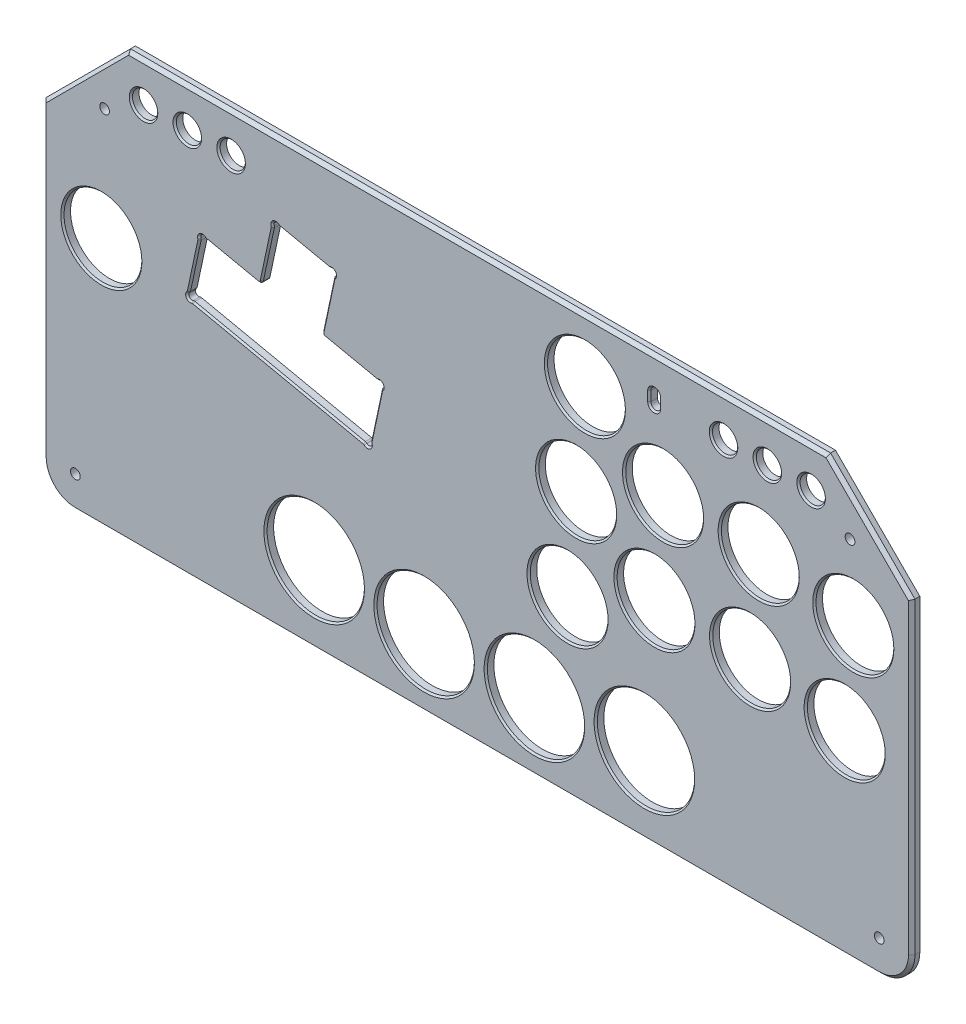
SolidWorks part; units mm, degrees
ref_plane "Front Plane" through (0, 0, 0) normal (0, 0, 1) x (1, 0, 0)
ref_plane "Top Plane" through (0, 0, 0) normal (0, 1, 0) x (1, 0, 0)
ref_plane "Right Plane" through (0, 0, 0) normal (1, 0, 0) x (0, 0, -1)
sketch "Sketch1" plane through (0, 0, 0) normal (0, 0, 1) x (1, 0, 0)
  line L0 (157.8919, 26.2701) -> (191.7747, 29.0915)
  line L1 (157.8919, 26.2701) -> (191.7747, 26.2701)
  line L2 (157.8919, 26.2701) -> (157.8919, 29.0915)
  line L3 (157.8919, 29.0915) -> (191.7747, 29.0915)
  line L4 (191.7747, 26.2701) -> (191.7747, 29.0915)
  line L5 (123.8919, 26.2701) -> (90.0092, 26.2701)
  line L6 (123.8919, 26.2701) -> (123.8919, 29.0915)
  line L7 (123.8919, 29.0915) -> (90.0092, 29.0915)
  line L8 (90.0092, 26.2701) -> (90.0092, 29.0915)
  line L9 (90.0092, 29.0915) -> (123.8919, 26.2701)
  line L10 (168.0919, 58.3601) -> (194.8735, 70.7292)
  line L11 (168.0919, 58.3601) -> (194.8735, 58.3601)
  line L12 (168.0919, 58.3601) -> (168.0919, 70.7292)
  line L13 (168.0919, 70.7292) -> (194.8735, 70.7292)
  line L14 (194.8735, 58.3601) -> (194.8735, 70.7292)
  line L15 (194.8735, 70.7292) -> (224.3587, 70.7292)
  line L16 (194.8735, 70.7292) -> (194.8735, 69.7923)
  line L17 (194.8735, 69.7923) -> (224.3587, 69.7923)
  line L18 (224.3587, 70.7292) -> (224.3587, 69.7923)
  line L19 (224.3587, 69.7923) -> (253.5106, 69.7923)
  line L20 (224.3587, 69.7923) -> (224.3587, 65.2742)
  line L21 (224.3587, 65.2742) -> (253.5106, 65.2742)
  line L22 (253.5106, 69.7923) -> (253.5106, 65.2742)
  line L23 (224.3587, 69.7923) -> (194.8735, 70.7292)
  line L24 (253.5106, 65.2742) -> (224.3587, 69.7923)
  line L25 (170.7502, 87.7401) -> (168.0919, 58.3601)
  line L26 (168.0919, 58.3601) -> (170.7502, 58.3601)
  line L27 (168.0919, 58.3601) -> (168.0919, 87.7401)
  line L28 (168.0919, 87.7401) -> (170.7502, 87.7401)
  line L29 (170.7502, 58.3601) -> (170.7502, 87.7401)
  line L30 (52.9966, 89.4705) -> (24.4119, 82.1791)
  line L31 (24.4119, 82.1791) -> (52.9966, 82.1791)
  line L32 (24.4119, 82.1791) -> (24.4119, 89.4705)
  line L33 (24.4119, 89.4705) -> (52.9966, 89.4705)
  line L34 (52.9966, 82.1791) -> (52.9966, 89.4705)
  line L35 (82.4966, 89.4705) -> (109.0019, 89.4705)
  line L36 (82.4966, 89.4705) -> (82.4966, 76.5201)
  line L37 (82.4966, 76.5201) -> (109.0019, 76.5201)
  line L38 (109.0019, 89.4705) -> (109.0019, 76.5201)
  line L39 (92.4554, 117.2387) -> (82.4966, 117.2387)
  line L40 (92.4554, 117.2387) -> (92.4554, 89.4705)
  line L41 (92.4554, 89.4705) -> (82.4966, 89.4705)
  line L42 (82.4966, 117.2387) -> (82.4966, 89.4705)
  line L43 (92.4554, 117.2387) -> (82.4966, 89.4705)
  line L44 (109.0019, 76.5201) -> (82.4966, 89.4705)
  circle A0 centre (123.8919, 26.2701) radius 14.25
  circle A1 centre (157.8919, 26.2701) radius 14.25
  circle A2 centre (90.0092, 29.0915) radius 14.25
  circle A3 centre (191.7747, 29.0915) radius 14.25
  circle A4 centre (82.4966, 89.4705) radius 11.25
  circle A5 centre (92.4554, 117.2387) radius 11.25
  circle A6 centre (52.9966, 89.4705) radius 11.25
  circle A7 centre (109.0019, 76.5201) radius 11.25
  circle A8 centre (24.4119, 82.1791) radius 11.25
  circle A9 centre (170.7502, 87.7401) radius 11.25
  circle A10 centre (168.0919, 58.3601) radius 11.25
  circle A11 centre (197.5318, 100.1092) radius 11.25
  circle A12 centre (194.8735, 70.7292) radius 11.25
  circle A13 centre (227.0169, 99.1723) radius 11.25
  circle A14 centre (224.3587, 69.7923) radius 11.25
  circle A15 centre (256.1689, 94.6541) radius 11.25
  circle A16 centre (253.5106, 65.2742) radius 11.25
  circle A17 centre (24.4119, 82.1791) radius 12
  circle A18 centre (52.9966, 89.4705) radius 12
  circle A19 centre (92.4554, 117.2387) radius 12
  circle A20 centre (82.4966, 89.4705) radius 12
  circle A21 centre (109.0019, 76.5201) radius 12
  circle A22 centre (168.0919, 58.3601) radius 12
  circle A23 centre (194.8735, 70.7292) radius 12
  circle A24 centre (224.3587, 69.7923) radius 12
  circle A25 centre (253.5106, 65.2742) radius 12
  circle A26 centre (256.1689, 94.6541) radius 12
  circle A27 centre (227.0169, 99.1723) radius 12
  circle A28 centre (197.5318, 100.1092) radius 12
  circle A29 centre (170.7502, 87.7401) radius 12
  circle A30 centre (191.7747, 29.0915) radius 15
  circle A31 centre (157.8919, 26.2701) radius 15
  circle A32 centre (123.8919, 26.2701) radius 15
  circle A33 centre (90.0092, 29.0915) radius 15
  circle A34 centre (173.429, 117.1182) radius 11.25
  circle A35 centre (173.429, 117.1182) radius 12
  dimension "D1" = 28.5
  dimension "D2" = 22.5
  dimension "D3" = 0.75
  dimension "D4" = 0.75
  dimension "D34" = 34
  dimension "D5" = 29.5
  dimension "D6" = 29.5
  dimension "D7" = 29.5
  dimension "D8" = 29.5
  dimension "D9" = 29.5
  dimension "D10" = 29.5
  dimension "D11" = 29.5
  dimension "D12" = 29.5
  dimension "D13" = 29.5
  dimension "D14" = 29.5
  dimension "D15" = 29.5
  dimension "D16" = 29.5
  dimension "D17" = 29.5
  dimension "D18" = 29.5
  dimension "D19" = 34
  dimension "D20" = 34
  dimension "D21" = 32.09
  dimension "D22" = 10.2
  dimension "D23" = 4.76
  dimension "D24" = 4.76
  dimension "D25" = 24.79
  dimension "D26" = 1.82
  dimension "D27" = 8.81
  dimension "D28" = 84.83
  dimension "D29" = 75.69
  dimension "D30" = 70.27
  dimension "D31" = 26.04
  dimension "D32" = 14.89
  dimension "D33" = 50.25
  dimension "D35" = 29.5
  dimension "D36" = 29.5
sketch "Sketch4" plane through (-30.2083, 20.075, 0) normal (0, 0, 1) x (0.9781, -0.2079, 0)
  line L0 (86.1706, 94.1917) -> (105.2206, 75.1417)
  line L1 (67.1206, 94.1917) -> (86.1706, 94.1917)
  line L2 (67.1206, 94.1917) -> (67.1206, 75.1417)
  line L3 (67.1206, 75.1417) -> (86.1706, 75.1417)
  line L4 (86.1706, 94.1917) -> (86.1706, 75.1417)
  line L5 (86.1706, 94.1917) -> (105.2206, 94.1917)
  line L6 (86.1706, 94.1917) -> (86.1706, 75.1417)
  line L7 (86.1706, 75.1417) -> (105.2206, 75.1417)
  line L8 (105.2206, 94.1917) -> (105.2206, 75.1417)
  line L9 (105.2206, 94.1917) -> (124.2706, 94.1917)
  line L10 (105.2206, 94.1917) -> (105.2206, 75.1417)
  line L11 (105.2206, 75.1417) -> (124.2706, 75.1417)
  line L12 (124.2706, 94.1917) -> (124.2706, 75.1417)
  line L13 (86.1706, 94.1917) -> (105.2206, 94.1917)
  line L14 (86.1706, 94.1917) -> (86.1706, 113.2417)
  line L15 (86.1706, 113.2417) -> (105.2206, 113.2417)
  line L16 (105.2206, 94.1917) -> (105.2206, 113.2417)
  line L17 (66.9585, 85.1784) -> (124.4326, 84.1551)
  point P14 (95.6956, 84.6667)
  point P15 (95.6956, 84.6667)
  dimension "D1" = 19.05
sketch "Sketch9" plane through (0, 0, 0) normal (0, 0, 1) x (1, 0, 0)
  line L1 (17.3619, 89.2291) -> (31.4619, 89.2291)
  line L2 (17.3619, 89.2291) -> (17.3619, 75.1291)
  line L3 (17.3619, 75.1291) -> (31.4619, 75.1291)
  line L4 (31.4619, 89.2291) -> (31.4619, 75.1291)
  line L5 (45.9466, 96.5205) -> (60.0466, 96.5205)
  line L6 (45.9466, 96.5205) -> (45.9466, 82.4205)
  line L7 (45.9466, 82.4205) -> (60.0466, 82.4205)
  line L8 (60.0466, 96.5205) -> (60.0466, 82.4205)
  line L9 (75.4466, 96.5205) -> (89.5466, 96.5205)
  line L10 (75.4466, 96.5205) -> (75.4466, 82.4205)
  line L11 (75.4466, 82.4205) -> (89.5466, 82.4205)
  line L12 (89.5466, 96.5205) -> (89.5466, 82.4205)
  line L13 (101.9519, 83.5701) -> (116.0519, 83.5701)
  line L14 (101.9519, 83.5701) -> (101.9519, 69.4701)
  line L15 (101.9519, 69.4701) -> (116.0519, 69.4701)
  line L16 (116.0519, 83.5701) -> (116.0519, 69.4701)
  line L17 (85.4054, 124.2887) -> (99.5054, 124.2887)
  line L18 (85.4054, 124.2887) -> (85.4054, 110.1887)
  line L19 (85.4054, 110.1887) -> (99.5054, 110.1887)
  line L20 (99.5054, 124.2887) -> (99.5054, 110.1887)
  line L21 (82.9592, 36.1415) -> (97.0592, 36.1415)
  line L22 (82.9592, 36.1415) -> (82.9592, 22.0415)
  line L23 (82.9592, 22.0415) -> (97.0592, 22.0415)
  line L24 (97.0592, 36.1415) -> (97.0592, 22.0415)
  line L25 (116.8419, 33.3201) -> (130.9419, 33.3201)
  line L26 (116.8419, 33.3201) -> (116.8419, 19.2201)
  line L27 (116.8419, 19.2201) -> (130.9419, 19.2201)
  line L28 (130.9419, 33.3201) -> (130.9419, 19.2201)
  line L29 (150.8419, 33.3201) -> (164.9419, 33.3201)
  line L30 (150.8419, 33.3201) -> (150.8419, 19.2201)
  line L31 (150.8419, 19.2201) -> (164.9419, 19.2201)
  line L32 (164.9419, 33.3201) -> (164.9419, 19.2201)
  line L33 (184.7247, 36.1415) -> (198.8247, 36.1415)
  line L34 (184.7247, 36.1415) -> (184.7247, 22.0415)
  line L35 (184.7247, 22.0415) -> (198.8247, 22.0415)
  line L36 (198.8247, 36.1415) -> (198.8247, 22.0415)
  line L37 (260.5606, 58.2242) -> (246.4606, 58.2242)
  line L38 (260.5606, 58.2242) -> (260.5606, 72.3242)
  line L39 (260.5606, 72.3242) -> (246.4606, 72.3242)
  line L40 (246.4606, 58.2242) -> (246.4606, 72.3242)
  line L41 (217.3087, 76.8423) -> (231.4087, 76.8423)
  line L42 (217.3087, 76.8423) -> (217.3087, 62.7423)
  line L43 (217.3087, 62.7423) -> (231.4087, 62.7423)
  line L44 (231.4087, 76.8423) -> (231.4087, 62.7423)
  line L45 (187.8235, 77.7792) -> (201.9235, 77.7792)
  line L46 (187.8235, 77.7792) -> (187.8235, 63.6792)
  line L47 (187.8235, 63.6792) -> (201.9235, 63.6792)
  line L48 (201.9235, 77.7792) -> (201.9235, 63.6792)
  line L49 (161.0419, 65.4101) -> (175.1419, 65.4101)
  line L50 (161.0419, 65.4101) -> (161.0419, 51.3101)
  line L51 (161.0419, 51.3101) -> (175.1419, 51.3101)
  line L52 (175.1419, 65.4101) -> (175.1419, 51.3101)
  line L53 (163.7002, 94.7901) -> (177.8002, 94.7901)
  line L54 (163.7002, 94.7901) -> (163.7002, 80.6901)
  line L55 (163.7002, 80.6901) -> (177.8002, 80.6901)
  line L56 (177.8002, 94.7901) -> (177.8002, 80.6901)
  line L57 (190.4818, 107.1592) -> (204.5818, 107.1592)
  line L58 (190.4818, 107.1592) -> (190.4818, 93.0592)
  line L59 (190.4818, 93.0592) -> (204.5818, 93.0592)
  line L60 (204.5818, 107.1592) -> (204.5818, 93.0592)
  line L61 (219.9669, 106.2223) -> (234.0669, 106.2223)
  line L62 (219.9669, 106.2223) -> (219.9669, 92.1223)
  line L63 (219.9669, 92.1223) -> (234.0669, 92.1223)
  line L64 (234.0669, 106.2223) -> (234.0669, 92.1223)
  line L65 (249.1189, 101.7041) -> (263.2189, 101.7041)
  line L66 (249.1189, 101.7041) -> (249.1189, 87.6041)
  line L67 (249.1189, 87.6041) -> (263.2189, 87.6041)
  line L68 (263.2189, 101.7041) -> (263.2189, 87.6041)
  line L69 (166.379, 124.1682) -> (180.479, 124.1682)
  line L70 (166.379, 124.1682) -> (166.379, 110.0682)
  line L71 (166.379, 110.0682) -> (180.479, 110.0682)
  line L72 (180.479, 124.1682) -> (180.479, 110.0682)
  point P72 (24.4119, 89.2291)
  point P74 (52.9966, 96.5205)
  point P76 (82.4966, 96.5205)
  point P78 (92.4554, 124.2887)
  point P80 (109.0019, 83.5701)
  point P82 (90.0092, 36.1415)
  point P84 (123.8919, 33.3201)
  point P86 (157.8919, 33.3201)
  point P88 (191.7747, 36.1415)
  point P90 (168.0919, 65.4101)
  point P92 (170.7502, 94.7901)
  point P94 (173.429, 124.1682)
  point P96 (197.5318, 107.1592)
  point P98 (227.0169, 106.2223)
  point P100 (256.1689, 101.7041)
  point P102 (194.8735, 77.7792)
  point P104 (224.3587, 76.8423)
  point P106 (253.5106, 72.3242)
  point P108 (17.3619, 82.1791)
  point P109 (45.9466, 89.4705)
  point P110 (75.4466, 89.4705)
  point P111 (101.9519, 76.5201)
  point P112 (85.4054, 117.2387)
  point P113 (82.9592, 29.0915)
  point P114 (116.8419, 26.2701)
  point P115 (150.8419, 26.2701)
  point P116 (184.7247, 29.0915)
  point P118 (161.0419, 58.3601)
  point P119 (187.8235, 70.7292)
  point P120 (217.3087, 69.7923)
  point P121 (246.4606, 65.2742)
  point P122 (163.7002, 87.7401)
  point P123 (190.4818, 100.1092)
  point P124 (219.9669, 99.1723)
  point P125 (249.1189, 94.6541)
  point P126 (166.379, 117.1182)
  dimension "D1" = 14.1
sketch "Sketch10" plane through (-22.0981, 19.3454, 0) normal (0, 0, 1) x (0.9781, -0.2079, 0)
  line L1 (61.5108, 90.7441) -> (75.6108, 90.7441)
  line L2 (61.5108, 90.7441) -> (61.5108, 76.6441)
  line L3 (61.5108, 76.6441) -> (75.6108, 76.6441)
  line L4 (75.6108, 90.7441) -> (75.6108, 76.6441)
  line L5 (80.5608, 90.7441) -> (94.6608, 90.7441)
  line L6 (80.5608, 90.7441) -> (80.5608, 76.6441)
  line L7 (80.5608, 76.6441) -> (94.6608, 76.6441)
  line L8 (94.6608, 90.7441) -> (94.6608, 76.6441)
  line L9 (99.6108, 90.7441) -> (113.7108, 90.7441)
  line L10 (99.6108, 90.7441) -> (99.6108, 76.6441)
  line L11 (99.6108, 76.6441) -> (113.7108, 76.6441)
  line L12 (113.7108, 90.7441) -> (113.7108, 76.6441)
  line L13 (80.5608, 109.7941) -> (94.6608, 109.7941)
  line L14 (80.5608, 109.7941) -> (80.5608, 95.6941)
  line L15 (80.5608, 95.6941) -> (94.6608, 95.6941)
  line L16 (94.6608, 109.7941) -> (94.6608, 95.6941)
  line L17 (50.5121, 89.6359) -> (53.4436, 75.8441) construction
  line L18 (59.0358, 93.2191) -> (78.0858, 93.2191) construction
  line L19 (78.0858, 112.2691) -> (97.1358, 112.2691) construction
  line L20 (97.1358, 93.2191) -> (116.1858, 93.2191) construction
  line L21 (78.0858, 93.2191) -> (78.0858, 112.2691) construction
  line L23 (59.0358, 93.2191) -> (59.0358, 74.1691) construction
  point P16 (75.6108, 83.6941)
  point P17 (94.6608, 83.6941)
  point P18 (113.7108, 83.6941)
  point P19 (87.6108, 90.7441)
  point P20 (87.6108, 109.7941)
  point P23 (68.5608, 90.7441)
  point P26 (68.5608, 93.2191)
  point P29 (87.6108, 112.2691)
  point P30 (106.6608, 90.7441)
  point P33 (106.6608, 93.2191)
  point P34 (80.5608, 102.7441)
  point P37 (78.0858, 102.7441)
  point P42 (59.0358, 83.6941)
  point P43 (61.5108, 83.6941)
sketch "Sketch14" plane through (0, 0, 0) normal (0, 0, 1) x (1, 0, 0)
  line L0 (165.1144, 80.6901) -> (163.7002, 82.1043)
  line L1 (163.7002, 93.3758) -> (165.1144, 94.7901)
  line L2 (177.8002, 93.3758) -> (176.386, 94.7901)
  line L3 (179.0648, 110.0682) -> (180.479, 111.4824)
  line L4 (166.379, 111.4824) -> (167.7932, 110.0682)
  line L5 (166.379, 122.754) -> (167.7932, 124.1682)
  line L6 (179.0648, 124.1682) -> (180.479, 122.754)
  line L7 (203.1676, 93.0592) -> (204.5818, 94.4734)
  line L8 (17.3619, 89.2291) -> (17.3619, 75.1291) construction
  line L9 (17.3619, 89.2291) -> (31.4619, 89.2291) construction
  line L10 (17.3619, 87.8149) -> (18.7761, 89.2291)
  line L11 (17.3619, 75.1291) -> (31.4619, 75.1291) construction
  line L12 (31.4619, 89.2291) -> (31.4619, 75.1291) construction
  line L13 (45.9466, 96.5205) -> (60.0466, 96.5205) construction
  line L14 (60.0466, 96.5205) -> (60.0466, 82.4205) construction
  line L15 (45.9466, 96.5205) -> (45.9466, 82.4205) construction
  line L16 (45.9466, 82.4205) -> (60.0466, 82.4205) construction
  line L17 (85.4054, 124.2887) -> (85.4054, 110.1887) construction
  line L18 (85.4054, 124.2887) -> (99.5054, 124.2887) construction
  line L19 (99.5054, 124.2887) -> (99.5054, 110.1887) construction
  line L20 (85.4054, 110.1887) -> (99.5054, 110.1887) construction
  line L21 (101.9519, 83.5701) -> (101.9519, 69.4701) construction
  line L22 (101.9519, 83.5701) -> (116.0519, 83.5701) construction
  line L23 (116.0519, 83.5701) -> (116.0519, 69.4701) construction
  line L24 (101.9519, 69.4701) -> (116.0519, 69.4701) construction
  line L25 (91.2712, 73.6044) -> (105.0631, 70.6729) construction
  line L26 (107.9947, 84.4647) -> (105.0631, 70.6729) construction
  line L27 (94.2028, 87.3963) -> (107.9947, 84.4647) construction
  line L28 (94.2028, 87.3963) -> (91.2712, 73.6044) construction
  line L29 (72.6375, 77.5651) -> (86.4294, 74.6336) construction
  line L30 (89.361, 88.4255) -> (86.4294, 74.6336) construction
  line L31 (75.5691, 91.357) -> (89.361, 88.4255) construction
  line L32 (75.5691, 91.357) -> (72.6375, 77.5651) construction
  line L33 (56.9354, 95.3177) -> (54.0038, 81.5259) construction
  line L34 (56.9354, 95.3177) -> (70.7273, 92.3862) construction
  line L35 (70.7273, 92.3862) -> (67.7957, 78.5943) construction
  line L36 (54.0038, 81.5259) -> (67.7957, 78.5943) construction
  line L37 (76.5983, 96.1988) -> (90.3901, 93.2673) construction
  line L38 (93.3217, 107.0592) -> (90.3901, 93.2673) construction
  line L39 (79.5298, 109.9907) -> (76.5983, 96.1988) construction
  line L40 (79.5298, 109.9907) -> (93.3217, 107.0592) construction
  line L41 (82.9592, 36.1415) -> (82.9592, 22.0415) construction
  line L42 (82.9592, 36.1415) -> (97.0592, 36.1415) construction
  line L43 (82.9592, 22.0415) -> (97.0592, 22.0415) construction
  line L44 (97.0592, 36.1415) -> (97.0592, 22.0415) construction
  line L45 (116.8419, 33.3201) -> (116.8419, 19.2201) construction
  line L46 (116.8419, 33.3201) -> (130.9419, 33.3201) construction
  line L47 (116.8419, 19.2201) -> (130.9419, 19.2201) construction
  line L48 (130.9419, 33.3201) -> (130.9419, 19.2201) construction
  line L49 (150.8419, 33.3201) -> (150.8419, 19.2201) construction
  line L50 (150.8419, 33.3201) -> (164.9419, 33.3201) construction
  line L51 (164.9419, 33.3201) -> (164.9419, 19.2201) construction
  line L52 (150.8419, 19.2201) -> (164.9419, 19.2201) construction
  line L53 (184.7247, 36.1415) -> (184.7247, 22.0415) construction
  line L54 (184.7247, 22.0415) -> (198.8247, 22.0415) construction
  line L55 (198.8247, 36.1415) -> (198.8247, 22.0415) construction
  line L56 (184.7247, 36.1415) -> (198.8247, 36.1415) construction
  line L57 (161.0419, 65.4101) -> (175.1419, 65.4101) construction
  line L58 (175.1419, 65.4101) -> (175.1419, 51.3101) construction
  line L59 (161.0419, 51.3101) -> (175.1419, 51.3101) construction
  line L60 (161.0419, 65.4101) -> (161.0419, 51.3101) construction
  line L61 (187.8235, 77.7792) -> (187.8235, 63.6792) construction
  line L62 (187.8235, 77.7792) -> (201.9235, 77.7792) construction
  line L63 (187.8235, 63.6792) -> (201.9235, 63.6792) construction
  line L64 (201.9235, 77.7792) -> (201.9235, 63.6792) construction
  line L65 (217.3087, 76.8423) -> (217.3087, 62.7423) construction
  line L66 (217.3087, 76.8423) -> (231.4087, 76.8423) construction
  line L67 (231.4087, 76.8423) -> (231.4087, 62.7423) construction
  line L68 (217.3087, 62.7423) -> (231.4087, 62.7423) construction
  line L69 (260.5606, 58.2242) -> (246.4606, 58.2242) construction
  line L70 (260.5606, 58.2242) -> (260.5606, 72.3242) construction
  line L71 (246.4606, 58.2242) -> (246.4606, 72.3242) construction
  line L72 (260.5606, 72.3242) -> (246.4606, 72.3242) construction
  line L73 (249.1189, 101.7041) -> (263.2189, 101.7041) construction
  line L74 (263.2189, 101.7041) -> (263.2189, 87.6041) construction
  line L75 (249.1189, 87.6041) -> (263.2189, 87.6041) construction
  line L76 (249.1189, 101.7041) -> (249.1189, 87.6041) construction
  line L77 (219.9669, 106.2223) -> (219.9669, 92.1223) construction
  line L78 (219.9669, 106.2223) -> (234.0669, 106.2223) construction
  line L79 (234.0669, 106.2223) -> (234.0669, 92.1223) construction
  line L80 (219.9669, 92.1223) -> (234.0669, 92.1223) construction
  line L81 (190.4818, 107.1592) -> (204.5818, 107.1592) construction
  line L82 (204.5818, 107.1592) -> (204.5818, 93.0592) construction
  line L83 (190.4818, 93.0592) -> (204.5818, 93.0592) construction
  line L84 (190.4818, 107.1592) -> (190.4818, 93.0592) construction
  line L85 (163.7002, 94.7901) -> (177.8002, 94.7901) construction
  line L86 (177.8002, 94.7901) -> (177.8002, 80.6901) construction
  line L87 (163.7002, 80.6901) -> (177.8002, 80.6901) construction
  line L88 (163.7002, 94.7901) -> (163.7002, 80.6901) construction
  line L89 (180.479, 124.1682) -> (180.479, 110.0682) construction
  line L90 (166.379, 110.0682) -> (180.479, 110.0682) construction
  line L91 (166.379, 124.1682) -> (166.379, 110.0682) construction
  line L92 (166.379, 124.1682) -> (180.479, 124.1682) construction
  line L93 (17.3619, 76.5433) -> (18.7761, 75.1291)
  line L94 (30.0477, 75.1291) -> (31.4619, 76.5433)
  line L95 (31.4619, 87.8149) -> (30.0477, 89.2291)
  line L96 (45.9466, 95.1063) -> (47.3608, 96.5205)
  line L97 (45.9466, 83.8347) -> (47.3608, 82.4205)
  line L98 (54.2979, 82.9092) -> (55.3871, 81.2318)
  line L99 (58.6323, 82.4205) -> (60.0466, 83.8347)
  line L100 (56.6413, 93.9344) -> (58.3187, 95.0237)
  line L101 (58.6323, 96.5205) -> (60.0466, 95.1063)
  line L102 (69.3439, 92.6802) -> (70.4332, 91.0029)
  line L103 (68.0897, 79.9776) -> (66.4124, 78.8883)
  line L104 (75.2751, 89.9737) -> (76.9524, 91.063)
  line L105 (72.9316, 78.9484) -> (74.0208, 77.2711)
  line L106 (85.0461, 74.9276) -> (86.7234, 76.0169)
  line L107 (89.0669, 87.0421) -> (87.9777, 88.7195)
  line L108 (89.0068, 93.5613) -> (90.6842, 94.6506)
  line L109 (76.8923, 97.5822) -> (77.9816, 95.9048)
  line L110 (91.9384, 107.3532) -> (93.0277, 105.6759)
  line L111 (79.2358, 108.6074) -> (80.9131, 109.6967)
  line L112 (85.4054, 111.6029) -> (86.8196, 110.1887)
  line L113 (98.0912, 110.1887) -> (99.5054, 111.6029)
  line L114 (98.0912, 124.2887) -> (99.5054, 122.8745)
  line L115 (85.4054, 122.8745) -> (86.8196, 124.2887)
  line L116 (93.9088, 86.013) -> (95.5861, 87.1023)
  line L117 (91.5653, 74.9877) -> (92.6546, 73.3104)
  line L118 (103.6798, 70.9669) -> (105.3572, 72.0562)
  line L119 (106.6114, 84.7588) -> (107.7006, 83.0814)
  line L120 (101.9519, 82.1559) -> (103.3662, 83.5701)
  line L121 (101.9519, 70.8843) -> (103.3662, 69.4701)
  line L122 (114.6377, 69.4701) -> (116.0519, 70.8843)
  line L123 (116.0519, 82.1559) -> (114.6377, 83.5701)
  line L124 (82.9592, 34.7272) -> (84.3734, 36.1415)
  line L125 (82.9592, 23.4557) -> (84.3734, 22.0415)
  line L126 (95.645, 22.0415) -> (97.0592, 23.4557)
  line L127 (97.0592, 34.7272) -> (95.645, 36.1415)
  line L128 (116.8419, 31.9059) -> (118.2562, 33.3201)
  line L129 (116.8419, 20.6343) -> (118.2562, 19.2201)
  line L130 (129.5277, 19.2201) -> (130.9419, 20.6343)
  line L131 (130.9419, 31.9059) -> (129.5277, 33.3201)
  line L132 (150.8419, 31.9059) -> (152.2562, 33.3201)
  line L133 (150.8419, 20.6343) -> (152.2562, 19.2201)
  line L134 (163.5277, 19.2201) -> (164.9419, 20.6343)
  line L135 (164.9419, 31.9059) -> (163.5277, 33.3201)
  line L136 (184.7247, 34.7272) -> (186.1389, 36.1415)
  line L137 (184.7247, 23.4557) -> (186.1389, 22.0415)
  line L138 (197.4105, 22.0415) -> (198.8247, 23.4557)
  line L139 (198.8247, 34.7272) -> (197.4105, 36.1415)
  line L140 (173.7277, 51.3101) -> (175.1419, 52.7243)
  line L141 (161.0419, 52.7243) -> (162.4562, 51.3101)
  line L142 (161.0419, 63.9959) -> (162.4562, 65.4101)
  line L143 (173.7277, 65.4101) -> (175.1419, 63.9959)
  line L144 (187.8235, 65.0934) -> (189.2378, 63.6792)
  line L145 (200.5093, 63.6792) -> (201.9235, 65.0934)
  line L146 (200.5093, 77.7792) -> (201.9235, 76.365)
  line L147 (187.8235, 76.365) -> (189.2378, 77.7792)
  line L148 (176.386, 80.6901) -> (177.8002, 82.1043)
  line L149 (204.5818, 105.745) -> (203.1676, 107.1592)
  line L150 (191.896, 107.1592) -> (190.4818, 105.745)
  line L151 (190.4818, 94.4734) -> (191.896, 93.0592)
  line L152 (219.9669, 104.8081) -> (221.3812, 106.2223)
  line L153 (232.6527, 106.2223) -> (234.0669, 104.8081)
  line L154 (234.0669, 93.5365) -> (232.6527, 92.1223)
  line L155 (219.9669, 93.5365) -> (221.3812, 92.1223)
  line L156 (229.9944, 76.8423) -> (231.4087, 75.4281)
  line L157 (217.3087, 75.4281) -> (218.7229, 76.8423)
  line L158 (217.3087, 64.1565) -> (218.7229, 62.7423)
  line L159 (229.9944, 62.7423) -> (231.4087, 64.1565)
  line L160 (259.1464, 72.3242) -> (260.5606, 70.9099)
  line L161 (246.4606, 70.9099) -> (247.8748, 72.3242)
  line L162 (259.1464, 58.2242) -> (260.5606, 59.6384)
  line L163 (247.8748, 58.2242) -> (246.4606, 59.6384)
  line L164 (261.8047, 87.6041) -> (263.2189, 89.0183)
  line L165 (249.1189, 89.0183) -> (250.5331, 87.6041)
  line L166 (249.1189, 100.2899) -> (250.5331, 101.7041)
  line L167 (261.8047, 101.7041) -> (263.2189, 100.2899)
  line L168 (75.4466, 96.5205) -> (75.4466, 82.4205) construction
  line L169 (75.4466, 96.5205) -> (89.5466, 96.5205) construction
  line L170 (89.5466, 96.5205) -> (89.5466, 82.4205) construction
  line L171 (75.4466, 82.4205) -> (89.5466, 82.4205) construction
  line L172 (76.8608, 96.5205) -> (75.4466, 95.1063)
  line L173 (88.1323, 96.5205) -> (89.5466, 95.1063)
  line L174 (89.5466, 83.8347) -> (88.1323, 82.4205)
  line L175 (75.4466, 83.8347) -> (76.8608, 82.4205)
  arc A0 (17.3619, 87.8149) -> (18.7761, 89.2291) centre (18.069, 88.522) cw
  arc A1 (18.7761, 75.1291) -> (17.3619, 76.5433) centre (18.069, 75.8362) cw
  arc A2 (31.4619, 76.5433) -> (30.0477, 75.1291) centre (30.7548, 75.8362) cw
  arc A3 (30.0477, 89.2291) -> (31.4619, 87.8149) centre (30.7548, 88.522) cw
  arc A4 (58.6323, 96.5205) -> (60.0466, 95.1063) centre (59.3394, 95.8134) cw
  arc A5 (45.9466, 95.1063) -> (47.3608, 96.5205) centre (46.6537, 95.8134) cw
  arc A6 (47.3608, 82.4205) -> (45.9466, 83.8347) centre (46.6537, 83.1276) cw
  arc A7 (60.0466, 83.8347) -> (58.6323, 82.4205) centre (59.3394, 83.1276) cw
  arc A8 (85.4054, 122.8745) -> (86.8196, 124.2887) centre (86.1125, 123.5816) cw
  arc A9 (98.0912, 124.2887) -> (99.5054, 122.8745) centre (98.7983, 123.5816) cw
  arc A10 (99.5054, 111.6029) -> (98.0912, 110.1887) centre (98.7983, 110.8958) cw
  arc A11 (85.4054, 111.6029) -> (86.8196, 110.1887) centre (86.1125, 110.8958) ccw
  arc A12 (101.9519, 82.1559) -> (103.3662, 83.5701) centre (102.6591, 82.863) cw
  arc A13 (114.6377, 83.5701) -> (116.0519, 82.1559) centre (115.3448, 82.863) cw
  arc A14 (116.0519, 70.8843) -> (114.6377, 69.4701) centre (115.3448, 70.1772) cw
  arc A15 (101.9519, 70.8843) -> (103.3662, 69.4701) centre (102.6591, 70.1772) ccw
  arc A16 (103.6798, 70.9669) -> (105.3572, 72.0562) centre (104.5185, 71.5115) ccw
  arc A17 (106.6114, 84.7588) -> (107.7006, 83.0814) centre (107.156, 83.9201) cw
  arc A18 (93.9088, 86.013) -> (95.5861, 87.1023) centre (94.7474, 86.5576) cw
  arc A19 (91.5653, 74.9877) -> (92.6546, 73.3104) centre (92.1099, 74.1491) ccw
  arc A20 (85.0461, 74.9276) -> (86.7234, 76.0169) centre (85.8848, 75.4722) ccw
  arc A21 (87.9777, 88.7195) -> (89.0669, 87.0421) centre (88.5223, 87.8808) cw
  arc A22 (75.2751, 89.9737) -> (76.9524, 91.063) centre (76.1137, 90.5183) cw
  arc A23 (72.9316, 78.9484) -> (74.0208, 77.2711) centre (73.4762, 78.1098) ccw
  arc A24 (56.6413, 93.9344) -> (58.3187, 95.0237) centre (57.48, 94.4791) cw
  arc A25 (69.3439, 92.6802) -> (70.4332, 91.0029) centre (69.8886, 91.8415) cw
  arc A26 (68.0897, 79.9776) -> (66.4124, 78.8883) centre (67.2511, 79.433) cw
  arc A27 (54.2979, 82.9092) -> (55.3871, 81.2318) centre (54.8425, 82.0705) ccw
  arc A28 (89.0068, 93.5613) -> (90.6842, 94.6506) centre (89.8455, 94.106) ccw
  arc A29 (76.8923, 97.5822) -> (77.9816, 95.9048) centre (77.4369, 96.7435) ccw
  arc A30 (79.2358, 108.6074) -> (80.9131, 109.6967) centre (80.0744, 109.1521) cw
  arc A31 (91.9384, 107.3532) -> (93.0277, 105.6759) centre (92.483, 106.5145) cw
  arc A32 (82.9592, 34.7272) -> (84.3734, 36.1415) centre (83.6663, 35.4344) cw
  arc A33 (82.9592, 23.4557) -> (84.3734, 22.0415) centre (83.6663, 22.7486) ccw
  arc A34 (95.645, 22.0415) -> (97.0592, 23.4557) centre (96.3521, 22.7486) ccw
  arc A35 (95.645, 36.1415) -> (97.0592, 34.7272) centre (96.3521, 35.4344) cw
  arc A36 (116.8419, 31.9059) -> (118.2562, 33.3201) centre (117.5491, 32.613) cw
  arc A37 (116.8419, 20.6343) -> (118.2562, 19.2201) centre (117.5491, 19.9272) ccw
  arc A38 (129.5277, 19.2201) -> (130.9419, 20.6343) centre (130.2348, 19.9272) ccw
  arc A39 (129.5277, 33.3201) -> (130.9419, 31.9059) centre (130.2348, 32.613) cw
  arc A40 (150.8419, 31.9059) -> (152.2562, 33.3201) centre (151.5491, 32.613) cw
  arc A41 (163.5277, 33.3201) -> (164.9419, 31.9059) centre (164.2348, 32.613) cw
  arc A42 (164.9419, 20.6343) -> (163.5277, 19.2201) centre (164.2348, 19.9272) cw
  arc A43 (150.8419, 20.6343) -> (152.2562, 19.2201) centre (151.5491, 19.9272) ccw
  arc A44 (184.7247, 23.4557) -> (186.1389, 22.0415) centre (185.4318, 22.7486) ccw
  arc A45 (197.4105, 22.0415) -> (198.8247, 23.4557) centre (198.1176, 22.7486) ccw
  arc A46 (197.4105, 36.1415) -> (198.8247, 34.7272) centre (198.1176, 35.4344) cw
  arc A47 (184.7247, 34.7272) -> (186.1389, 36.1415) centre (185.4318, 35.4344) cw
  arc A48 (173.7277, 65.4101) -> (175.1419, 63.9959) centre (174.4348, 64.703) cw
  arc A49 (175.1419, 52.7243) -> (173.7277, 51.3101) centre (174.4348, 52.0172) cw
  arc A50 (161.0419, 52.7243) -> (162.4562, 51.3101) centre (161.7491, 52.0172) ccw
  arc A51 (161.0419, 63.9959) -> (162.4562, 65.4101) centre (161.7491, 64.703) cw
  arc A52 (187.8235, 76.365) -> (189.2378, 77.7792) centre (188.5306, 77.0721) cw
  arc A53 (187.8235, 65.0934) -> (189.2378, 63.6792) centre (188.5306, 64.3863) ccw
  arc A54 (200.5093, 63.6792) -> (201.9235, 65.0934) centre (201.2164, 64.3863) ccw
  arc A55 (200.5093, 77.7792) -> (201.9235, 76.365) centre (201.2164, 77.0721) cw
  arc A56 (217.3087, 75.4281) -> (218.7229, 76.8423) centre (218.0158, 76.1352) cw
  arc A57 (229.9944, 76.8423) -> (231.4087, 75.4281) centre (230.7016, 76.1352) cw
  arc A58 (231.4087, 64.1565) -> (229.9944, 62.7423) centre (230.7016, 63.4494) cw
  arc A59 (217.3087, 64.1565) -> (218.7229, 62.7423) centre (218.0158, 63.4494) ccw
  arc A60 (259.1464, 58.2242) -> (260.5606, 59.6384) centre (259.8535, 58.9313) ccw
  arc A61 (246.4606, 59.6384) -> (247.8748, 58.2242) centre (247.1677, 58.9313) ccw
  arc A62 (246.4606, 70.9099) -> (247.8748, 72.3242) centre (247.1677, 71.617) cw
  arc A63 (259.1464, 72.3242) -> (260.5606, 70.9099) centre (259.8535, 71.617) cw
  arc A64 (261.8047, 101.7041) -> (263.2189, 100.2899) centre (262.5118, 100.997) cw
  arc A65 (263.2189, 89.0183) -> (261.8047, 87.6041) centre (262.5118, 88.3112) cw
  arc A66 (250.5331, 87.6041) -> (249.1189, 89.0183) centre (249.826, 88.3112) cw
  arc A67 (249.1189, 100.2899) -> (250.5331, 101.7041) centre (249.826, 100.997) cw
  arc A68 (219.9669, 104.8081) -> (221.3812, 106.2223) centre (220.674, 105.5152) cw
  arc A69 (232.6527, 106.2223) -> (234.0669, 104.8081) centre (233.3598, 105.5152) cw
  arc A70 (234.0669, 93.5365) -> (232.6527, 92.1223) centre (233.3598, 92.8294) cw
  arc A71 (221.3812, 92.1223) -> (219.9669, 93.5365) centre (220.674, 92.8294) cw
  arc A72 (203.1676, 107.1592) -> (204.5818, 105.745) centre (203.8747, 106.4521) cw
  arc A73 (204.5818, 94.4734) -> (203.1676, 93.0592) centre (203.8747, 93.7663) cw
  arc A74 (191.896, 93.0592) -> (190.4818, 94.4734) centre (191.1889, 93.7663) cw
  arc A75 (190.4818, 105.745) -> (191.896, 107.1592) centre (191.1889, 106.4521) cw
  arc A76 (176.386, 94.7901) -> (177.8002, 93.3758) centre (177.0931, 94.0829) cw
  arc A77 (177.8002, 82.1043) -> (176.386, 80.6901) centre (177.0931, 81.3972) cw
  arc A78 (165.1144, 80.6901) -> (163.7002, 82.1043) centre (164.4073, 81.3972) cw
  arc A79 (163.7002, 93.3758) -> (165.1144, 94.7901) centre (164.4073, 94.0829) cw
  arc A80 (180.479, 111.4824) -> (179.0648, 110.0682) centre (179.7719, 110.7753) cw
  arc A81 (167.7932, 110.0682) -> (166.379, 111.4824) centre (167.0861, 110.7753) cw
  arc A82 (179.0648, 124.1682) -> (180.479, 122.754) centre (179.7719, 123.4611) cw
  arc A83 (166.379, 122.754) -> (167.7932, 124.1682) centre (167.0861, 123.4611) cw
  arc A84 (75.4466, 95.1063) -> (76.8608, 96.5205) centre (76.1537, 95.8134) cw
  arc A85 (88.1323, 96.5205) -> (89.5466, 95.1063) centre (88.8394, 95.8134) cw
  arc A86 (89.5466, 83.8347) -> (88.1323, 82.4205) centre (88.8394, 83.1276) cw
  arc A87 (76.8608, 82.4205) -> (75.4466, 83.8347) centre (76.1537, 83.1276) cw
  dimension "D1" = 45
  dimension "D2" = 1
  dimension "D71" = 45
  dimension "D3" = 45
  dimension "D4" = 45
  dimension "D5" = 45
  dimension "D6" = 45
  dimension "D7" = 45
  dimension "D8" = 45
  dimension "D9" = 45
  dimension "D10" = 45
  dimension "D11" = 45
  dimension "D12" = 45
  dimension "D13" = 45
  dimension "D14" = 45
  dimension "D15" = 45
  dimension "D16" = 45
  dimension "D17" = 45
  dimension "D18" = 45
  dimension "D19" = 45
  dimension "D20" = 45
  dimension "D21" = 45
  dimension "D22" = 45
  dimension "D23" = 45
  dimension "D24" = 45
  dimension "D25" = 45
  dimension "D26" = 45
  dimension "D27" = 45
  dimension "D28" = 45
  dimension "D29" = 45
  dimension "D30" = 45
  dimension "D31" = 45
  dimension "D32" = 45
  dimension "D33" = 45
  dimension "D34" = 45
  dimension "D35" = 45
  dimension "D36" = 45
  dimension "D37" = 45
  dimension "D38" = 45
  dimension "D39" = 45
  dimension "D40" = 45
  dimension "D41" = 45
  dimension "D42" = 45
  dimension "D43" = 45
  dimension "D44" = 45
  dimension "D45" = 45
  dimension "D46" = 45
  dimension "D47" = 45
  dimension "D48" = 45
  dimension "D49" = 45
  dimension "D50" = 45
  dimension "D51" = 45
  dimension "D52" = 45
  dimension "D53" = 45
  dimension "D54" = 45
  dimension "D55" = 45
  dimension "D56" = 45
  dimension "D57" = 45
  dimension "D58" = 45
  dimension "D59" = 45
  dimension "D60" = 45
  dimension "D61" = 45
  dimension "D62" = 45
  dimension "D63" = 45
  dimension "D64" = 45
  dimension "D65" = 45
  dimension "D66" = 45
  dimension "D67" = 45
  dimension "D68" = 45
  dimension "D69" = 45
  dimension "D70" = 45
  dimension "D72" = 45
  dimension "D73" = 45
  dimension "D74" = 45
  dimension "D75" = 45
  dimension "D76" = 45
  dimension "D77" = 45
  dimension "D78" = 45
  dimension "D79" = 45
  dimension "D80" = 45
  dimension "D81" = 45
  dimension "D82" = 45
  dimension "D83" = 45
  dimension "D84" = 45
  dimension "D85" = 45
  dimension "D86" = 45
  dimension "D87" = 45
  dimension "D88" = 45
  dimension "D89" = 45
sketch "Sketch16" plane through (0, 0, 0) normal (0, 0, 1) x (1, 0, 0)
  line L0 (81.0092, 30.6915) -> (99.0092, 30.6915)
  line L5 (17.3619, 89.2291) -> (17.3619, 75.1291) construction
  line L6 (81.0092, 30.6915) -> (81.0092, 27.4915)
  line L7 (17.3619, 75.1291) -> (31.4619, 75.1291) construction
  line L8 (15.4119, 83.7791) -> (33.4119, 83.7791)
  line L9 (15.4119, 83.7791) -> (15.4119, 80.5791)
  line L10 (15.4119, 80.5791) -> (33.4119, 80.5791)
  line L11 (33.4119, 83.7791) -> (33.4119, 80.5791)
  line L12 (81.0092, 27.4915) -> (99.0092, 27.4915)
  line L13 (99.0092, 30.6915) -> (99.0092, 27.4915)
  line L14 (114.8919, 27.8701) -> (132.8919, 27.8701)
  line L15 (114.8919, 27.8701) -> (114.8919, 24.6701)
  line L16 (114.8919, 24.6701) -> (132.8919, 24.6701)
  line L17 (132.8919, 27.8701) -> (132.8919, 24.6701)
  line L18 (148.8919, 27.8701) -> (166.8919, 27.8701)
  line L19 (148.8919, 27.8701) -> (148.8919, 24.6701)
  line L20 (148.8919, 24.6701) -> (166.8919, 24.6701)
  line L21 (166.8919, 27.8701) -> (166.8919, 24.6701)
  line L22 (182.7747, 30.6915) -> (200.7747, 30.6915)
  line L23 (182.7747, 30.6915) -> (182.7747, 27.4915)
  line L24 (182.7747, 27.4915) -> (200.7747, 27.4915)
  line L25 (200.7747, 30.6915) -> (200.7747, 27.4915)
  line L26 (43.9966, 91.0705) -> (61.9966, 91.0705)
  line L27 (43.9966, 91.0705) -> (43.9966, 87.8705)
  line L28 (43.9966, 87.8705) -> (61.9966, 87.8705)
  line L29 (61.9966, 91.0705) -> (61.9966, 87.8705)
  line L30 (73.4966, 91.0705) -> (91.4966, 91.0705)
  line L31 (73.4966, 91.0705) -> (73.4966, 87.8705)
  line L32 (73.4966, 87.8705) -> (91.4966, 87.8705)
  line L33 (91.4966, 91.0705) -> (91.4966, 87.8705)
  line L34 (100.0019, 78.1201) -> (118.0019, 78.1201)
  line L35 (100.0019, 78.1201) -> (100.0019, 74.9201)
  line L36 (100.0019, 74.9201) -> (118.0019, 74.9201)
  line L37 (118.0019, 78.1201) -> (118.0019, 74.9201)
  line L38 (83.4554, 118.8387) -> (101.4554, 118.8387)
  line L39 (83.4554, 118.8387) -> (83.4554, 115.6387)
  line L40 (83.4554, 115.6387) -> (101.4554, 115.6387)
  line L41 (101.4554, 118.8387) -> (101.4554, 115.6387)
  line L42 (164.429, 118.7182) -> (182.429, 118.7182)
  line L43 (164.429, 118.7182) -> (164.429, 115.5182)
  line L44 (164.429, 115.5182) -> (182.429, 115.5182)
  line L45 (182.429, 118.7182) -> (182.429, 115.5182)
  line L46 (161.7502, 89.3401) -> (179.7502, 89.3401)
  line L47 (161.7502, 89.3401) -> (161.7502, 86.1401)
  line L48 (161.7502, 86.1401) -> (179.7502, 86.1401)
  line L49 (179.7502, 89.3401) -> (179.7502, 86.1401)
  line L50 (188.5318, 101.7092) -> (206.5318, 101.7092)
  line L51 (188.5318, 101.7092) -> (188.5318, 98.5092)
  line L52 (188.5318, 98.5092) -> (206.5318, 98.5092)
  line L53 (206.5318, 101.7092) -> (206.5318, 98.5092)
  line L54 (159.0919, 59.9601) -> (177.0919, 59.9601)
  line L55 (159.0919, 59.9601) -> (159.0919, 56.7601)
  line L56 (159.0919, 56.7601) -> (177.0919, 56.7601)
  line L57 (177.0919, 59.9601) -> (177.0919, 56.7601)
  line L58 (185.8735, 72.3292) -> (203.8735, 72.3292)
  line L59 (185.8735, 72.3292) -> (185.8735, 69.1292)
  line L60 (185.8735, 69.1292) -> (203.8735, 69.1292)
  line L61 (203.8735, 72.3292) -> (203.8735, 69.1292)
  line L62 (218.0169, 100.7723) -> (236.0169, 100.7723)
  line L63 (218.0169, 100.7723) -> (218.0169, 97.5723)
  line L64 (218.0169, 97.5723) -> (236.0169, 97.5723)
  line L65 (236.0169, 100.7723) -> (236.0169, 97.5723)
  line L66 (215.3587, 71.3923) -> (233.3587, 71.3923)
  line L67 (215.3587, 71.3923) -> (215.3587, 68.1923)
  line L68 (215.3587, 68.1923) -> (233.3587, 68.1923)
  line L69 (233.3587, 71.3923) -> (233.3587, 68.1923)
  line L70 (247.1689, 96.2541) -> (265.1689, 96.2541)
  line L71 (247.1689, 96.2541) -> (247.1689, 93.0541)
  line L72 (247.1689, 93.0541) -> (265.1689, 93.0541)
  line L73 (265.1689, 96.2541) -> (265.1689, 93.0541)
  line L74 (244.5106, 66.8742) -> (262.5106, 66.8742)
  line L75 (244.5106, 66.8742) -> (244.5106, 63.6742)
  line L76 (244.5106, 63.6742) -> (262.5106, 63.6742)
  line L77 (262.5106, 66.8742) -> (262.5106, 63.6742)
  circle A0 centre (15.4119, 82.1791) radius 1.6
  circle A1 centre (33.4119, 82.1791) radius 1.6
  circle A2 centre (81.0092, 29.0915) radius 1.6
  circle A3 centre (99.0092, 29.0915) radius 1.6
  circle A4 centre (114.8919, 26.2701) radius 1.6
  circle A5 centre (132.8919, 26.2701) radius 1.6
  circle A6 centre (148.8919, 26.2701) radius 1.6
  circle A7 centre (166.8919, 26.2701) radius 1.6
  circle A8 centre (182.7747, 29.0915) radius 1.6
  circle A9 centre (200.7747, 29.0915) radius 1.6
  circle A10 centre (43.9966, 89.4705) radius 1.6
  circle A11 centre (61.9966, 89.4705) radius 1.6
  circle A12 centre (73.4966, 89.4705) radius 1.6
  circle A13 centre (91.4966, 89.4705) radius 1.6
  circle A14 centre (100.0019, 76.5201) radius 1.6
  circle A15 centre (118.0019, 76.5201) radius 1.6
  circle A16 centre (83.4554, 117.2387) radius 1.6
  circle A17 centre (101.4554, 117.2387) radius 1.6
  circle A18 centre (164.429, 117.1182) radius 1.6
  circle A19 centre (182.429, 117.1182) radius 1.6
  circle A20 centre (161.7502, 87.7401) radius 1.6
  circle A21 centre (179.7502, 87.7401) radius 1.6
  circle A22 centre (188.5318, 100.1092) radius 1.6
  circle A23 centre (206.5318, 100.1092) radius 1.6
  circle A24 centre (159.0919, 58.3601) radius 1.6
  circle A25 centre (177.0919, 58.3601) radius 1.6
  circle A26 centre (185.8735, 70.7292) radius 1.6
  circle A27 centre (203.8735, 70.7292) radius 1.6
  circle A28 centre (218.0169, 99.1723) radius 1.6
  circle A29 centre (236.0169, 99.1723) radius 1.6
  circle A30 centre (215.3587, 69.7923) radius 1.6
  circle A31 centre (233.3587, 69.7923) radius 1.6
  circle A32 centre (247.1689, 94.6541) radius 1.6
  circle A33 centre (265.1689, 94.6541) radius 1.6
  circle A34 centre (244.5106, 65.2742) radius 1.6
  circle A35 centre (262.5106, 65.2742) radius 1.6
  point P2 (24.4119, 75.1291)
  point P6 (17.3619, 82.1791)
  point P14 (24.4119, 80.5791)
  point P53 (90.0092, 30.6915)
  point P57 (123.8919, 27.8701)
  point P60 (157.8919, 27.8701)
  point P63 (191.7747, 30.6915)
  point P73 (52.9966, 91.0705)
  point P83 (82.4966, 91.0705)
  point P93 (109.0019, 78.1201)
  point P103 (92.4554, 118.8387)
  point P113 (173.429, 118.7182)
  point P123 (170.7502, 89.3401)
  point P133 (197.5318, 101.7092)
  point P143 (168.0919, 59.9601)
  point P153 (194.8735, 72.3292)
  point P163 (227.0169, 100.7723)
  point P173 (224.3587, 71.3923)
  point P183 (256.1689, 96.2541)
  point P193 (253.5106, 66.8742)
  dimension "D1" = 3.2
  dimension "D2" = 18
sketch "Sketch8" plane through (0, 0, 0) normal (0, 0, 1) x (1, 0, 0)
  line L0 (52.2844, 74.6389) -> (82.4966, 89.4705)
  line L1 (86.9403, 110.9459) -> (79.0189, 73.6784)
  line L2 (77.6235, 112.9262) -> (96.2572, 108.9655) construction
  line L3 (69.702, 75.6588) -> (88.3357, 71.6981) construction
  line L4 (53.3861, 72.3947) -> (55.5425, 73.4534)
  line L5 (99.6829, 63.2465) -> (101.1557, 61.3487)
  line L6 (103.1308, 62.8814) -> (82.4966, 89.4705)
  line L13 (93.9017, 130.158) -> (94.0202, 130.4883)
  line L14 (99.5495, 128.1325) -> (99.6679, 128.4628)
  line L16 (99.4417, 62.7418) -> (100.7607, 61.0421)
  line L17 (55.5377, 72.894) -> (53.6064, 71.9459)
  line L19 (82.4966, 89.4705) -> (96.8441, 129.4755)
  circle A1 centre (57.4203, 106.4022) radius 2.5
  circle A2 centre (106.0456, 106.2134) radius 2.5
  circle A3 centre (76.7673, 63.0854) radius 2.5
  circle A4 centre (52.9966, 89.4705) radius 13
  circle A6 centre (92.4554, 117.2387) radius 13
  circle A7 centre (109.0019, 76.5201) radius 13
  circle A8 centre (82.4966, 89.4705) radius 25
  arc A10 (50.3337, 102.1949) -> (81.377, 124.0408) centre (40.5107, 149.1329) ccw
  circle A11 centre (103.1308, 62.8814) radius 2.5
  circle A12 centre (52.2844, 74.6389) radius 2.5
  circle A13 centre (96.8441, 129.4755) radius 2.5
  circle A14 centre (52.2844, 74.6389) radius 3
  circle A15 centre (103.1308, 62.8814) radius 3
  circle A16 centre (96.8441, 129.4755) radius 3
  arc A17 (104.9258, 113.5659) -> (115.3756, 87.8504) centre (126.3001, 107.2707) ccw
  arc A18 (45.7038, 78.7088) -> (110.8301, 63.6492) centre (97.7768, 155.5511) ccw
  circle A19 centre (92.4554, 117.2387) radius 15
  circle A20 centre (109.0019, 76.5201) radius 15
  circle A21 centre (52.9966, 89.4705) radius 15
  circle A22 centre (82.4966, 89.4705) radius 27
  arc A23 (44.5818, 77.0531) -> (111.1113, 61.6691) centre (97.7768, 155.5511) ccw
  arc A24 (49.924, 104.1525) -> (79.6727, 125.0873) centre (40.5107, 149.1329) ccw
  arc A25 (106.8443, 113.0008) -> (116.3562, 89.5935) centre (126.3001, 107.2707) ccw
  circle A26 centre (52.9966, 89.4705) radius 12.5
  circle A27 centre (109.0019, 76.5201) radius 12.5
  circle A28 centre (92.4554, 117.2387) radius 12.5
  circle A29 centre (82.4966, 89.4705) radius 24.5
  arc A30 (104.4462, 113.7071) -> (115.1305, 87.4146) centre (126.3001, 107.2707) ccw
  arc A31 (110.7597, 64.1443) -> (45.9842, 79.1227) centre (97.7768, 155.5511) cw
  arc A32 (50.4361, 101.7055) -> (81.8031, 123.7792) centre (40.5107, 149.1329) ccw
  circle A33 centre (52.9966, 89.4705) radius 15.5
  circle A34 centre (109.0019, 76.5201) radius 15.5
  circle A35 centre (92.4554, 117.2387) radius 15.5
  circle A36 centre (82.4966, 89.4705) radius 27.5
  arc A37 (107.3239, 112.8596) -> (116.6013, 90.0293) centre (126.3001, 107.2707) ccw
  arc A38 (111.1816, 61.1741) -> (44.3013, 76.6392) centre (97.7768, 155.5511) cw
  arc A39 (49.8216, 104.6419) -> (79.2466, 125.349) centre (40.5107, 149.1329) ccw
  circle A40 centre (106.0456, 106.2134) radius 3
  circle A41 centre (76.7673, 63.0854) radius 3
  circle A42 centre (57.4203, 106.4022) radius 3
  dimension "D3" = 26
  dimension "D4" = 5
  dimension "D7" = 6
  dimension "D8" = 50
  dimension "D1" = 2
  dimension "D2" = 2
  dimension "D5" = 0.5
  dimension "D6" = 0.5
  dimension "D9" = 0.5
  dimension "D10" = 0.5
sketch "Sketch2" plane through (0, 0, 0) normal (0, 0, 1) x (1, 0, 0)
  line L0 (30.4119, 134.2387) -> (8.4119, 112.2387)
  line L1 (16.4119, 134.2387) -> (264.1689, 134.2387)
  line L2 (8.4119, 126.2387) -> (8.4119, 15.2864)
  line L3 (16.4119, 7.2864) -> (264.1689, 7.2864)
  line L4 (272.1689, 126.2387) -> (272.1689, 15.2864)
  line L5 (16.4119, 136.2387) -> (264.1689, 136.2387)
  line L6 (6.4119, 126.2387) -> (6.4119, 15.2864)
  line L7 (16.4119, 5.2864) -> (264.1689, 5.2864)
  line L8 (274.1689, 126.2387) -> (274.1689, 15.2864)
  line L9 (250.1689, 134.2387) -> (272.1689, 112.2387)
  line L10 (6.4119, 110.2387) -> (32.4119, 136.2387)
  line L11 (248.1689, 136.2387) -> (274.1689, 110.2387)
  line L12 (6.4119, 107.4103) -> (35.2403, 136.2387)
  line L13 (245.3405, 136.2387) -> (274.1689, 107.4103)
  circle A0 centre (24.4119, 82.1791) radius 12 construction
  circle A2 centre (256.1689, 94.6541) radius 12 construction
  arc A3 (264.1689, 136.2387) -> (274.1689, 126.2387) centre (264.1689, 126.2387) cw
  circle A4 centre (123.8919, 26.2701) radius 15 construction
  arc A5 (264.1689, 5.2864) -> (274.1689, 15.2864) centre (264.1689, 15.2864) ccw
  arc A6 (6.4119, 15.2864) -> (16.4119, 5.2864) centre (16.4119, 15.2864) ccw
  arc A7 (16.4119, 136.2387) -> (6.4119, 126.2387) centre (16.4119, 126.2387) ccw
  arc A8 (264.1689, 134.2387) -> (272.1689, 126.2387) centre (264.1689, 126.2387) cw
  arc A9 (264.1689, 7.2864) -> (272.1689, 15.2864) centre (264.1689, 15.2864) ccw
  arc A10 (8.4119, 15.2864) -> (16.4119, 7.2864) centre (16.4119, 15.2864) ccw
  arc A11 (16.4119, 134.2387) -> (8.4119, 126.2387) centre (16.4119, 126.2387) ccw
  circle A12 centre (92.4554, 117.2387) radius 13 construction
  point P4 (12.4119, 82.1791)
  point P5 (92.4554, 130.2387)
  point P8 (268.1689, 94.6541)
  point P14 (124.5912, 11.2864)
  point P36 (30.4119, 134.2387)
  point P39 (250.1689, 134.2387)
  dimension "D9" = 10
  dimension "D10" = 8
  dimension "D1" = 4
  dimension "D2" = 4
  dimension "D3" = 4
  dimension "D4" = 4
  dimension "D5" = 2
  dimension "D6" = 2
  dimension "D7" = 2
  dimension "D8" = 2
  dimension "D11" = 14
  dimension "D12" = 45
  dimension "D13" = 14
  dimension "D14" = 45
  dimension "D15" = 2
  dimension "D16" = 2
sketch "Sketch6" plane through (0, 0, 0) normal (0, 0, 1) x (1, 0, 0)
  line L0 (44.9119, 130.2387) -> (56.9119, 130.2387)
  line L1 (31.4119, 130.2387) -> (43.4119, 130.2387)
  line L2 (31.4119, 130.2387) -> (31.4119, 118.2387)
  line L3 (31.4119, 118.2387) -> (43.4119, 118.2387)
  line L4 (43.4119, 130.2387) -> (43.4119, 118.2387)
  line L5 (34.1619, 133.2387) -> (40.6619, 133.2387)
  line L6 (34.1619, 133.2387) -> (34.1619, 115.2387)
  line L7 (34.1619, 115.2387) -> (40.6619, 115.2387)
  line L8 (40.6619, 133.2387) -> (40.6619, 115.2387)
  line L9 (44.9119, 130.2387) -> (44.9119, 118.2387)
  line L10 (44.9119, 118.2387) -> (56.9119, 118.2387)
  line L11 (56.9119, 130.2387) -> (56.9119, 118.2387)
  line L12 (47.6619, 133.2387) -> (54.1619, 133.2387)
  line L13 (47.6619, 133.2387) -> (47.6619, 115.2387)
  line L14 (47.6619, 115.2387) -> (54.1619, 115.2387)
  line L15 (54.1619, 133.2387) -> (54.1619, 115.2387)
  line L16 (58.4119, 130.2387) -> (70.4119, 130.2387)
  line L17 (58.4119, 130.2387) -> (58.4119, 118.2387)
  line L18 (58.4119, 118.2387) -> (70.4119, 118.2387)
  line L19 (70.4119, 130.2387) -> (70.4119, 118.2387)
  line L20 (61.1619, 133.2387) -> (67.6619, 133.2387)
  line L21 (61.1619, 133.2387) -> (61.1619, 115.2387)
  line L22 (61.1619, 115.2387) -> (67.6619, 115.2387)
  line L23 (67.6619, 133.2387) -> (67.6619, 115.2387)
  line L24 (237.1689, 130.2387) -> (249.1689, 130.2387)
  line L25 (237.1689, 130.2387) -> (237.1689, 118.2387)
  line L26 (237.1689, 118.2387) -> (249.1689, 118.2387)
  line L27 (249.1689, 130.2387) -> (249.1689, 118.2387)
  line L28 (239.9189, 133.2387) -> (246.4189, 133.2387)
  line L29 (239.9189, 133.2387) -> (239.9189, 115.2387)
  line L30 (239.9189, 115.2387) -> (246.4189, 115.2387)
  line L31 (246.4189, 133.2387) -> (246.4189, 115.2387)
  line L32 (223.6689, 130.2387) -> (235.6689, 130.2387)
  line L33 (223.6689, 130.2387) -> (223.6689, 118.2387)
  line L34 (223.6689, 118.2387) -> (235.6689, 118.2387)
  line L35 (235.6689, 130.2387) -> (235.6689, 118.2387)
  line L36 (226.4189, 133.2387) -> (232.9189, 133.2387)
  line L37 (226.4189, 133.2387) -> (226.4189, 115.2387)
  line L38 (226.4189, 115.2387) -> (232.9189, 115.2387)
  line L39 (232.9189, 133.2387) -> (232.9189, 115.2387)
  line L40 (210.1689, 130.2387) -> (222.1689, 130.2387)
  line L41 (210.1689, 130.2387) -> (210.1689, 118.2387)
  line L42 (210.1689, 118.2387) -> (222.1689, 118.2387)
  line L43 (222.1689, 130.2387) -> (222.1689, 118.2387)
  line L44 (212.9189, 133.2387) -> (219.4189, 133.2387)
  line L45 (212.9189, 133.2387) -> (212.9189, 115.2387)
  line L46 (212.9189, 115.2387) -> (219.4189, 115.2387)
  line L47 (219.4189, 133.2387) -> (219.4189, 115.2387)
  line L48 (16.4119, 134.2387) -> (264.1689, 134.2387) construction
  line L49 (8.4119, 126.2387) -> (8.4119, 15.2864) construction
  line L50 (272.1689, 126.2387) -> (272.1689, 15.2864) construction
  circle A0 centre (37.4119, 124.2387) radius 3.4
  circle A1 centre (50.9119, 124.2387) radius 3.4
  circle A2 centre (64.4119, 124.2387) radius 3.4
  circle A3 centre (243.1689, 124.2387) radius 3.4
  circle A4 centre (229.6689, 124.2387) radius 3.4
  circle A5 centre (216.1689, 124.2387) radius 3.4
  point P8 (37.4119, 130.2387)
  point P9 (37.4119, 133.2387)
  point P10 (34.1619, 124.2387)
  point P11 (31.4119, 124.2387)
  point P15 (43.4119, 124.2387)
  point P43 (243.1689, 130.2387)
  point P44 (243.1689, 133.2387)
  point P45 (239.9189, 124.2387)
  point P46 (237.1689, 124.2387)
  point P50 (249.1689, 124.2387)
  dimension "D4" = 6.8
  dimension "D9" = 6.8
  dimension "D1" = 18
  dimension "D2" = 12
  dimension "D3" = 6.5
  dimension "D5" = 3
  dimension "D6" = 18
  dimension "D7" = 12
  dimension "D8" = 6.5
  dimension "D11" = 1
  dimension "D12" = 23
  dimension "D13" = 23
  dimension "D10" = 3
sketch "Sketch13" plane through (0, 0, 0) normal (0, 0, 1) x (1, 0, 0)
  line L1 (115.4554, 133.7387) -> (125.4554, 133.7387)
  line L2 (110.4554, 128.7387) -> (110.4554, 118.7387)
  line L3 (115.4554, 113.7387) -> (125.4554, 113.7387)
  line L4 (130.4554, 128.7387) -> (130.4554, 118.7387)
  line L5 (115.9854, 134.7387) -> (124.9254, 134.7387)
  line L6 (115.9854, 134.7387) -> (115.9854, 127.3887)
  line L7 (115.9854, 127.3887) -> (124.9254, 127.3887)
  line L8 (124.9254, 134.7387) -> (124.9254, 127.3887)
  line L9 (115.5354, 132.9887) -> (116.4354, 132.9887)
  line L10 (115.5354, 132.9887) -> (115.5354, 131.2887)
  line L11 (115.5354, 131.2887) -> (116.4354, 131.2887)
  line L12 (116.4354, 132.9887) -> (116.4354, 131.2887)
  line L13 (114.4554, 120.2387) -> (126.4554, 120.2387)
  line L14 (114.4554, 120.2387) -> (114.4554, 113.7387)
  line L15 (114.4554, 113.7387) -> (126.4554, 113.7387)
  line L16 (126.4554, 120.2387) -> (126.4554, 113.7387)
  line L19 (115.4554, 134.2387) -> (125.4554, 134.2387)
  line L20 (109.9554, 128.7387) -> (109.9554, 118.7387)
  line L21 (115.4554, 113.2387) -> (125.4554, 113.2387)
  line L22 (130.9554, 128.7387) -> (130.9554, 118.7387)
  line L23 (16.4119, 134.2387) -> (264.1689, 134.2387) construction
  arc A0 (125.4554, 134.2387) -> (130.9554, 128.7387) centre (125.4554, 128.7387) cw
  arc A1 (115.4554, 133.7387) -> (110.4554, 128.7387) centre (115.4554, 128.7387) ccw
  arc A2 (125.4554, 133.7387) -> (130.4554, 128.7387) centre (125.4554, 128.7387) cw
  arc A3 (125.4554, 113.7387) -> (130.4554, 118.7387) centre (125.4554, 118.7387) ccw
  arc A4 (110.4554, 118.7387) -> (115.4554, 113.7387) centre (115.4554, 118.7387) ccw
  circle A6 centre (112.9554, 123.7387) radius 2.5
  circle A7 centre (127.9554, 123.7387) radius 2.5
  arc A8 (125.4554, 113.2387) -> (130.9554, 118.7387) centre (125.4554, 118.7387) ccw
  arc A9 (109.9554, 118.7387) -> (115.4554, 113.2387) centre (115.4554, 118.7387) ccw
  arc A10 (115.4554, 134.2387) -> (109.9554, 128.7387) centre (115.4554, 128.7387) ccw
  circle A12 centre (92.4554, 117.2387) radius 15.5 construction
  point P9 (115.9854, 132.1387)
  point P13 (116.4354, 132.1387)
  point P14 (115.9854, 132.9887)
  point P15 (120.4554, 113.7387)
  point P16 (120.4554, 127.3887)
  point P17 (120.4554, 113.7387)
  point P34 (110.4554, 123.7387)
  point P41 (120.4554, 134.2387)
  point P42 (120.4554, 133.7387)
  point P43 (130.9554, 123.7387)
  point P44 (130.4554, 123.7387)
  point P53 (107.9554, 117.2387)
  dimension "D7" = 6.5
  dimension "D10" = 5
  dimension "D11" = 5
  dimension "D17" = 5.5
  dimension "D1" = 8.94
  dimension "D2" = 7.35
  dimension "D3" = 2.6
  dimension "D4" = 1.7
  dimension "D5" = 0.9
  dimension "D6" = 1
  dimension "D8" = 12
  dimension "D9" = 7.15
  dimension "D12" = 20
  dimension "D13" = 20
  dimension "D14" = 2
  dimension "D15" = 0.5
  dimension "D16" = 0.5
sketch "Sketch5" plane through (0, 0, 0) normal (0, 0, 1) x (1, 0, 0)
  line L0 (130.9554, 128.7387) -> (130.9554, 118.7387) construction
  line L1 (136.9554, 138.2387) -> (158.5554, 138.2387)
  line L2 (136.9554, 138.2387) -> (136.9554, 106.9387)
  line L3 (136.9554, 106.9387) -> (158.5554, 106.9387)
  line L4 (158.5554, 138.2387) -> (158.5554, 106.9387)
  line L5 (141.7554, 106.9387) -> (153.7554, 106.9387)
  line L6 (141.7554, 106.9387) -> (141.7554, 93.2387)
  line L7 (141.7554, 93.2387) -> (153.7554, 93.2387)
  line L8 (153.7554, 106.9387) -> (153.7554, 93.2387)
  line L9 (16.4119, 136.2387) -> (264.1689, 136.2387) construction
  line L11 (139.9804, 102.2387) -> (155.5304, 102.2387)
  line L12 (139.9804, 102.2387) -> (139.9804, 91.2387)
  line L13 (139.9804, 91.2387) -> (155.5304, 91.2387)
  line L14 (155.5304, 102.2387) -> (155.5304, 91.2387)
  point P8 (147.7554, 106.9387)
  point P9 (147.7554, 106.9387)
  point P18 (147.7554, 93.2387)
  point P19 (147.7554, 102.2387)
  dimension "D1" = 6
  dimension "D2" = 2
  dimension "D3" = 31.3
  dimension "D4" = 21.6
  dimension "D5" = 12
  dimension "D6" = 13.7
  dimension "D7" = 15.55
  dimension "D8" = 11
  dimension "D9" = 2
sketch "Sketch3" plane through (0, 0, 0) normal (0, 0, 1) x (1, 0, 0)
  line L0 (123.8919, 26.2701) -> (157.8919, 26.2701)
  line L1 (125.5419, 80.2945) -> (156.2419, 80.2945)
  line L2 (125.5419, 80.2945) -> (125.5419, 57.0345)
  line L3 (125.5419, 57.0345) -> (156.2419, 57.0345)
  line L4 (156.2419, 80.2945) -> (156.2419, 57.0345)
  line L5 (133.1419, 59.0345) -> (148.6419, 59.0345)
  line L6 (133.1419, 59.0345) -> (133.1419, 55.0345)
  line L7 (133.1419, 55.0345) -> (148.6419, 55.0345)
  line L8 (148.6419, 59.0345) -> (148.6419, 55.0345)
  line L9 (129.0199, 77.1945) -> (152.7639, 77.1945)
  line L10 (129.0199, 77.1945) -> (129.0199, 64.3305)
  line L11 (129.0199, 64.3305) -> (152.7639, 64.3305)
  line L12 (152.7639, 77.1945) -> (152.7639, 64.3305)
  line L13 (133.1419, 55.0345) -> (130.8952, 55.0345)
  line L14 (130.8919, 61.7345) -> (150.8919, 61.7345)
  line L15 (130.8919, 61.7345) -> (130.8919, 56.2345)
  line L16 (130.8919, 56.2345) -> (150.8919, 56.2345)
  line L17 (150.8919, 61.7345) -> (150.8919, 56.2345)
  line L18 (127.5419, 78.2945) -> (154.2419, 78.2945)
  line L19 (130.8919, 56.2345) -> (150.8919, 56.2345)
  line L23 (127.5419, 78.2945) -> (127.5419, 59.0345)
  line L24 (127.5419, 59.0345) -> (154.2419, 59.0345)
  line L25 (154.2419, 78.2945) -> (154.2419, 59.0345)
  line L26 (130.8952, 59.0345) -> (150.8887, 59.0345)
  line L27 (130.8952, 59.0345) -> (130.8952, 53.0345)
  line L28 (130.8952, 53.0345) -> (150.8887, 53.0345)
  line L29 (150.8887, 59.0345) -> (150.8887, 53.0345)
  line L30 (148.6419, 55.0345) -> (150.8887, 55.0345)
  line L31 (274.1689, 126.2387) -> (274.1689, 15.2864) construction
  point P16 (140.8919, 55.0345)
  point P17 (140.8919, 57.0345)
  point P18 (140.8919, 64.3305)
  point P19 (140.8919, 26.2701)
  point P24 (140.8919, 56.2345)
  point P31 (140.8919, 78.2945)
  point P33 (140.8919, 80.2945)
  point P35 (140.8919, 59.0345)
  point P36 (125.5419, 68.6645)
  point P37 (127.5419, 68.6645)
  point P39 (130.8952, 54.0345)
  point P41 (150.8919, 59.0345)
  point P46 (274.1689, 70.7625)
  point P47 (152.7639, 70.7625)
  dimension "D1" = 30.7
  dimension "D2" = 23.26
  dimension "D3" = 4
  dimension "D4" = 15.5
  dimension "D5" = 12.864
  dimension "D6" = 23.744
  dimension "D7" = 26.7
  dimension "D8" = 20
  dimension "D9" = 5.5
  dimension "D10" = 6
  dimension "D11" = 1
  dimension "D12" = 2.8
  dimension "D13" = 19.26
  dimension "D14" = 1.1
  dimension "D15" = 5
sketch "Sketch15" plane through (0, 0, 0) normal (0, 0, 1) x (1, 0, 0)
  line L0 (25.4223, 117.2283) -> (255.1585, 117.2283)
  line L1 (16.4119, 15.2864) -> (264.1689, 15.2864)
  line L2 (16.4119, 7.2864) -> (264.1689, 7.2864) construction
  line L4 (6.4119, 107.4103) -> (35.2403, 136.2387) construction
  line L5 (20.8261, 121.8245) -> (25.4223, 117.2283)
  circle A0 centre (25.4223, 117.2283) radius 2.5
  circle A1 centre (255.1585, 117.2283) radius 2.5
  circle A2 centre (264.1689, 15.2864) radius 2.5
  circle A3 centre (16.4119, 15.2864) radius 2.5
  point P8 (140.2904, 117.2283)
  point P9 (140.2904, 15.2864)
  point P12 (140.2904, 7.2864)
  dimension "D1" = 5
  dimension "D2" = 6.5
  dimension "D3" = 90
sketch "Sketch18" plane through (0, 0, 0) normal (0, 0, 1) x (1, 0, 0)
  line L0 (125.5419, 63.0854) -> (125.5419, 99.9387)
  line L1 (130.5419, 104.9387) -> (156.429, 104.9387)
  line L2 (161.429, 109.9387) -> (161.429, 128.7387)
  line L3 (166.429, 133.7387) -> (246.3049, 133.7387)
  line L6 (268.1689, 107.7283) -> (268.1689, 58.2742)
  line L7 (263.1689, 53.2742) -> (211.7747, 53.2742)
  line L8 (206.7747, 48.2742) -> (206.7747, 16.2701)
  line L9 (201.7747, 11.2701) -> (80.0092, 11.2701)
  line L10 (75.0092, 16.2701) -> (75.0092, 33.0854)
  line L11 (70.0092, 38.0854) -> (17.4119, 38.0854)
  line L12 (12.4119, 43.0854) -> (12.4119, 107.7283)
  line L15 (34.2758, 133.7387) -> (71.4119, 133.7387)
  line L16 (76.4119, 128.7387) -> (76.4119, 122.5671)
  line L17 (68.5834, 114.7387) -> (61.4119, 114.7387)
  line L18 (36.4119, 89.7387) -> (36.4119, 63.0854)
  line L19 (41.4119, 58.0854) -> (120.5419, 58.0854)
  line L20 (16.4119, 134.2387) -> (264.1689, 134.2387) construction
  line L21 (250.6585, 129.3851) -> (250.6585, 117.7283)
  line L24 (47.6619, 115.2387) -> (54.1619, 115.2387) construction
  line L25 (239.9189, 133.2387) -> (246.4189, 133.2387) construction
  line L26 (255.6585, 112.7283) -> (263.1689, 112.7283)
  line L27 (24.9223, 112.7283) -> (17.4119, 112.7283)
  line L29 (125.5419, 80.2945) -> (125.5419, 57.0345) construction
  line L30 (32.8616, 133.1529) -> (30.5081, 130.7994)
  line L31 (75.8261, 121.1529) -> (69.9977, 115.3245)
  line L32 (6.4119, 107.4103) -> (35.2403, 136.2387) construction
  line L33 (25.4223, 117.2283) -> (255.1585, 117.2283) construction
  line L35 (27.9119, 126.7387) -> (29.9223, 126.7387)
  line L36 (27.9119, 126.7387) -> (27.9119, 121.7387)
  line L37 (27.9119, 121.7387) -> (29.9223, 121.7387)
  line L40 (247.7191, 133.1529) -> (250.0727, 130.7994)
  line L41 (252.6689, 126.7387) -> (250.6585, 126.7387)
  line L42 (252.6689, 126.7387) -> (252.6689, 121.7387)
  line L43 (252.6689, 121.7387) -> (250.6585, 121.7387)
  line L44 (250.6585, 126.7387) -> (250.6585, 121.7387)
  line L45 (245.3405, 136.2387) -> (274.1689, 107.4103) construction
  line L46 (256.1689, 94.6541) -> (253.5106, 65.2742)
  line L47 (123.8919, 26.2701) -> (157.8919, 26.2701) construction
  line L48 (29.9223, 129.3851) -> (29.9223, 126.7387)
  line L49 (29.9223, 121.7387) -> (29.9223, 117.7283)
  line L50 (20.8261, 121.8245) -> (25.4223, 117.2283) construction
  line L51 (136.9554, 106.9387) -> (158.5554, 106.9387) construction
  line L52 (31.4119, 130.2387) -> (31.4119, 118.2387) construction
  line L53 (70.4119, 130.2387) -> (70.4119, 118.2387) construction
  line L54 (210.1689, 130.2387) -> (210.1689, 118.2387) construction
  line L55 (249.1689, 130.2387) -> (249.1689, 118.2387) construction
  circle A0 centre (73.9119, 124.2387) radius 2.5
  circle A1 centre (255.1585, 117.2283) radius 2.5 construction
  circle A2 centre (24.4119, 82.1791) radius 12 construction
  circle A3 centre (90.0092, 29.0915) radius 15 construction
  circle A4 centre (157.8919, 26.2701) radius 15 construction
  circle A5 centre (191.7747, 29.0915) radius 15 construction
  circle A6 centre (253.5106, 65.2742) radius 12 construction
  circle A7 centre (256.1689, 94.6541) radius 12 construction
  circle A8 centre (173.429, 117.1182) radius 12 construction
  circle A9 centre (76.7673, 63.0854) radius 3 construction
  arc A12 (61.4119, 114.7387) -> (36.4119, 89.7387) centre (61.4119, 89.7387) ccw
  arc A15 (268.1689, 58.2742) -> (263.1689, 53.2742) centre (263.1689, 58.2742) cw
  arc A16 (80.0092, 11.2701) -> (75.0092, 16.2701) centre (80.0092, 16.2701) cw
  arc A17 (206.7747, 16.2701) -> (201.7747, 11.2701) centre (201.7747, 16.2701) cw
  arc A18 (211.7747, 53.2742) -> (206.7747, 48.2742) centre (211.7747, 48.2742) ccw
  arc A19 (161.429, 128.7387) -> (166.429, 133.7387) centre (166.429, 128.7387) cw
  arc A20 (156.429, 104.9387) -> (161.429, 109.9387) centre (156.429, 109.9387) ccw
  arc A21 (125.5419, 99.9387) -> (130.5419, 104.9387) centre (130.5419, 99.9387) cw
  arc A22 (125.5419, 63.0854) -> (120.5419, 58.0854) centre (120.5419, 63.0854) cw
  arc A23 (75.0092, 33.0854) -> (70.0092, 38.0854) centre (70.0092, 33.0854) ccw
  arc A24 (36.4119, 63.0854) -> (41.4119, 58.0854) centre (41.4119, 63.0854) ccw
  arc A25 (17.4119, 38.0854) -> (12.4119, 43.0854) centre (17.4119, 43.0854) cw
  circle A33 centre (27.9119, 124.2387) radius 2.5
  arc A34 (29.9223, 117.7283) -> (24.9223, 112.7283) centre (24.9223, 117.7283) cw
  arc A35 (12.4119, 107.7283) -> (17.4119, 112.7283) centre (17.4119, 107.7283) cw
  arc A36 (268.1689, 107.7283) -> (263.1689, 112.7283) centre (263.1689, 107.7283) ccw
  circle A37 centre (25.4223, 117.2283) radius 2.5 construction
  circle A38 centre (17.4119, 43.0854) radius 2.5
  circle A39 centre (140.8919, 16.2701) radius 2.5
  circle A40 centre (130.5419, 99.9387) radius 2.5
  circle A41 centre (252.6689, 124.2387) radius 2.5
  circle A42 centre (206.6689, 124.2387) radius 2.5
  circle A43 centre (263.1689, 79.9641) radius 2.5
  arc A44 (250.6585, 117.7283) -> (255.6585, 112.7283) centre (255.6585, 117.7283) ccw
  arc A45 (32.8616, 133.1529) -> (34.2758, 133.7387) centre (34.2758, 131.7387) cw
  arc A46 (30.5081, 130.7994) -> (29.9223, 129.3851) centre (31.9223, 129.3851) ccw
  arc A47 (250.0727, 130.7994) -> (250.6585, 129.3851) centre (248.6585, 129.3851) cw
  arc A48 (247.7191, 133.1529) -> (246.3049, 133.7387) centre (246.3049, 131.7387) ccw
  circle A49 centre (28.9223, 120.7387) radius 1
  circle A50 centre (28.9223, 127.7387) radius 1
  circle A51 centre (251.6585, 127.7387) radius 1
  circle A52 centre (251.6585, 120.7387) radius 1
  arc A53 (75.8261, 121.1529) -> (76.4119, 122.5671) centre (74.4119, 122.5671) ccw
  arc A54 (69.9977, 115.3245) -> (68.5834, 114.7387) centre (68.5834, 116.7387) cw
  arc A55 (71.4119, 133.7387) -> (76.4119, 128.7387) centre (71.4119, 128.7387) cw
  point P5 (250.6585, 133.7387)
  point P6 (25.4223, 114.7283)
  point P16 (29.9223, 133.7387)
  point P18 (76.4119, 114.7387)
  point P52 (76.7673, 60.0854)
  point P67 (27.9223, 117.2283)
  point P110 (252.6585, 117.2283)
  point P111 (255.1585, 114.7283)
  point P134 (254.8397, 79.9641)
  point P142 (140.8919, 26.2701)
  point P162 (76.4119, 121.7387)
  point P165 (69.4119, 114.7387)
  dimension "D3" = 5
  dimension "D5" = 0.5
  dimension "D10" = 2
  dimension "D11" = 25
  dimension "D12" = 5
  dimension "D13" = 2
  dimension "D6" = 2
  dimension "D9" = 2
  dimension "D17" = 5
  dimension "D19" = 2
  dimension "D20" = 2
  dimension "D21" = 2
  dimension "D1" = 0.5
  dimension "D2" = 0.5
  dimension "D4" = 0.5
  dimension "D7" = 2
  dimension "D8" = 20
  dimension "D15" = 2
  dimension "D16" = 0.5
  dimension "D18" = 5
  dimension "D22" = 3.5
  dimension "D23" = 3.5
  dimension "D24" = 3.5
  dimension "D25" = 3.5
sketch "Sketch19" plane through (0, 0, 0) normal (0, 0, 1) x (1, 0, 0)
  line L0 (11.9119, 107.7283) -> (11.9119, 43.0854)
  line L1 (17.4119, 37.5854) -> (70.0092, 37.5854)
  line L2 (74.5092, 33.0854) -> (74.5092, 16.2701)
  line L3 (80.0092, 10.7701) -> (201.7747, 10.7701)
  line L4 (207.2747, 16.2701) -> (207.2747, 48.2742)
  line L5 (211.7747, 52.7742) -> (263.1689, 52.7742)
  line L6 (268.6689, 58.2742) -> (268.6689, 107.7283)
  line L7 (263.1689, 113.2283) -> (255.6585, 113.2283)
  line L9 (70.0092, 38.0854) -> (17.4119, 38.0854) construction
  line L12 (24.9223, 113.2283) -> (17.4119, 113.2283)
  line L13 (24.9223, 112.7283) -> (17.4119, 112.7283) construction
  line L14 (75.0092, 16.2701) -> (75.0092, 33.0854) construction
  line L15 (16.4119, 134.2387) -> (264.1689, 134.2387) construction
  line L16 (12.4119, 43.0854) -> (12.4119, 107.7283) construction
  line L17 (201.7747, 11.2701) -> (80.0092, 11.2701) construction
  line L18 (206.7747, 48.2742) -> (206.7747, 16.2701) construction
  line L19 (263.1689, 53.2742) -> (211.7747, 53.2742) construction
  line L20 (268.1689, 107.7283) -> (268.1689, 58.2742) construction
  line L21 (255.6585, 112.7283) -> (263.1689, 112.7283) construction
  line L22 (251.1585, 117.7283) -> (251.1585, 121.2387)
  line L23 (245.3405, 136.2387) -> (274.1689, 107.4103) construction
  line L24 (248.0727, 133.5065) -> (250.4262, 131.1529)
  line L25 (246.3049, 134.2387) -> (166.429, 134.2387)
  line L26 (250.6585, 129.3851) -> (250.6585, 117.7283) construction
  line L27 (251.1585, 129.3851) -> (251.1585, 127.2387)
  line L28 (251.1585, 127.2387) -> (252.6689, 127.2387)
  line L29 (251.1585, 121.2387) -> (252.6689, 121.2387)
  line L30 (252.6689, 121.7387) -> (250.6585, 121.7387) construction
  line L31 (252.6689, 126.7387) -> (250.6585, 126.7387) construction
  line L32 (160.929, 128.7387) -> (160.929, 109.9387)
  line L33 (156.429, 105.4387) -> (130.5419, 105.4387)
  line L34 (125.0419, 99.9387) -> (125.0419, 63.0854)
  line L35 (120.5419, 58.5854) -> (41.4119, 58.5854)
  line L36 (36.9119, 63.0854) -> (36.9119, 89.7387)
  line L37 (61.4119, 114.2387) -> (68.5834, 114.2387)
  line L38 (76.9119, 122.5671) -> (76.9119, 128.7387)
  line L39 (71.4119, 134.2387) -> (34.2758, 134.2387)
  line L40 (76.4119, 128.7387) -> (76.4119, 122.5671) construction
  line L41 (68.5834, 114.7387) -> (61.4119, 114.7387) construction
  line L42 (70.3512, 114.9709) -> (76.1796, 120.7994)
  line L43 (32.5081, 133.5065) -> (30.1545, 131.1529)
  line L44 (75.8261, 121.1529) -> (69.9977, 115.3245) construction
  line L45 (36.4119, 89.7387) -> (36.4119, 63.0854) construction
  line L46 (41.4119, 58.0854) -> (120.5419, 58.0854) construction
  line L47 (125.5419, 63.0854) -> (125.5419, 99.9387) construction
  line L48 (130.5419, 104.9387) -> (156.429, 104.9387) construction
  line L49 (161.429, 109.9387) -> (161.429, 128.7387) construction
  line L50 (166.429, 134.2387) -> (71.4119, 134.2387)
  line L52 (6.4119, 107.4103) -> (35.2403, 136.2387) construction
  line L53 (29.4223, 117.7283) -> (29.4223, 121.2387)
  line L54 (29.4223, 129.3851) -> (29.4223, 127.2387)
  line L55 (29.9223, 129.3851) -> (29.9223, 126.7387) construction
  line L56 (27.9119, 126.7387) -> (29.9223, 126.7387) construction
  line L57 (29.4223, 127.2387) -> (27.9119, 127.2387)
  line L58 (29.4223, 121.2387) -> (27.9119, 121.2387)
  line L59 (27.9119, 121.7387) -> (29.9223, 121.7387) construction
  line L60 (252.6689, 126.7387) -> (252.6689, 121.7387) construction
  arc A0 (252.6689, 127.2387) -> (252.6689, 121.2387) centre (252.6689, 124.2387) cw
  arc A2 (251.1585, 129.3851) -> (250.4262, 131.1529) centre (248.6585, 129.3851) ccw
  arc A3 (248.0727, 133.5065) -> (246.3049, 134.2387) centre (246.3049, 131.7387) ccw
  arc A4 (251.1585, 117.7283) -> (255.6585, 113.2283) centre (255.6585, 117.7283) ccw
  arc A7 (247.7191, 133.1529) -> (246.3049, 133.7387) centre (246.3049, 131.7387) ccw construction
  arc A8 (27.9119, 121.2387) -> (27.9119, 127.2387) centre (27.9119, 124.2387) cw
  arc A9 (76.1796, 120.7994) -> (76.9119, 122.5671) centre (74.4119, 122.5671) ccw
  arc A10 (70.3512, 114.9709) -> (68.5834, 114.2387) centre (68.5834, 116.7387) cw
  arc A11 (30.1545, 131.1529) -> (29.4223, 129.3851) centre (31.9223, 129.3851) ccw
  arc A12 (32.5081, 133.5065) -> (34.2758, 134.2387) centre (34.2758, 131.7387) cw
  arc A13 (125.0419, 63.0854) -> (120.5419, 58.5854) centre (120.5419, 63.0854) cw
  arc A14 (160.929, 109.9387) -> (156.429, 105.4387) centre (156.429, 109.9387) cw
  arc A15 (130.5419, 105.4387) -> (125.0419, 99.9387) centre (130.5419, 99.9387) ccw
  arc A16 (166.429, 134.2387) -> (160.929, 128.7387) centre (166.429, 128.7387) ccw
  arc A17 (268.6689, 107.7283) -> (263.1689, 113.2283) centre (263.1689, 107.7283) ccw
  arc A18 (263.1689, 52.7742) -> (268.6689, 58.2742) centre (263.1689, 58.2742) ccw
  arc A19 (207.2747, 48.2742) -> (211.7747, 52.7742) centre (211.7747, 48.2742) cw
  arc A20 (201.7747, 10.7701) -> (207.2747, 16.2701) centre (201.7747, 16.2701) ccw
  arc A21 (74.5092, 16.2701) -> (80.0092, 10.7701) centre (80.0092, 16.2701) ccw
  arc A22 (11.9119, 43.0854) -> (17.4119, 37.5854) centre (17.4119, 43.0854) ccw
  arc A23 (41.4119, 58.5854) -> (36.9119, 63.0854) centre (41.4119, 63.0854) cw
  arc A24 (11.9119, 107.7283) -> (17.4119, 113.2283) centre (17.4119, 107.7283) cw
  arc A25 (29.4223, 117.7283) -> (24.9223, 113.2283) centre (24.9223, 117.7283) cw
  arc A26 (36.9119, 89.7387) -> (61.4119, 114.2387) centre (61.4119, 89.7387) cw
  arc A27 (76.9119, 128.7387) -> (71.4119, 134.2387) centre (71.4119, 128.7387) ccw
  arc A28 (70.0092, 37.5854) -> (74.5092, 33.0854) centre (70.0092, 33.0854) cw
  circle A29 centre (251.9085, 120.4887) radius 0.75
  circle A30 centre (251.9085, 127.9887) radius 0.75
  circle A31 centre (28.6723, 120.4887) radius 0.75
  circle A32 centre (28.6723, 127.9887) radius 0.75
  point P13 (29.4223, 134.2387)
  point P55 (251.1585, 130.4207)
  point P58 (247.3405, 134.2387)
  point P66 (76.9119, 114.2387)
  point P122 (160.929, 134.2387)
  point P145 (76.9119, 134.2387)
  dimension "D10" = 0.5
  dimension "D13" = 1.5
  dimension "D14" = 0.5
  dimension "D24" = 0.5
  dimension "D25" = 2.5
  dimension "D26" = 4.5
  dimension "D27" = 24.5
  dimension "D28" = 5.5
  dimension "D1" = 0.5
  dimension "D2" = 0.5
  dimension "D3" = 0.5
  dimension "D4" = 0.5
  dimension "D5" = 0.5
  dimension "D6" = 0.5
  dimension "D7" = 0.5
  dimension "D8" = 0.5
  dimension "D9" = 0.5
  dimension "D11" = 0.5
  dimension "D12" = 0.5
  dimension "D15" = 0.5
  dimension "D16" = 0.5
  dimension "D17" = 0.5
  dimension "D20" = 0.5
  dimension "D18" = 0.5
  dimension "D19" = 0.5
  dimension "D21" = 0.5
  dimension "D22" = 0.5
  dimension "D23" = 0.5
sketch "Sketch22" plane through (0, 0, 0) normal (0, 0, 1) x (1, 0, 0)
  line L0 (114.4554, 120.2387) -> (126.4554, 120.2387) construction
  line L1 (125.5419, 94.8666) -> (132.0419, 94.8666)
  line L2 (125.5419, 94.8666) -> (125.5419, 82.8666)
  line L3 (125.5419, 82.8666) -> (132.0419, 82.8666)
  line L4 (132.0419, 94.8666) -> (132.0419, 82.8666)
  line L5 (108.5419, 58.0854) -> (120.5419, 58.0854)
  line L6 (108.5419, 58.0854) -> (108.5419, 51.5854)
  line L7 (108.5419, 51.5854) -> (120.5419, 51.5854)
  line L8 (120.5419, 58.0854) -> (120.5419, 51.5854)
  line L9 (126.4554, 120.2387) -> (126.4554, 113.7387) construction
  line L10 (130.5419, 97.4387) -> (130.5419, 80.2945)
  line L11 (125.5419, 80.2945) -> (156.2419, 80.2945) construction
  line L14 (125.5419, 63.0854) -> (125.5419, 99.9387) construction
  circle A0 centre (130.5419, 99.9387) radius 2.5 construction
  point P19 (130.5419, 88.8666)
  point P21 (125.5419, 88.8666)
sketch "Sketch23" plane through (-19.0974, 26.7768, 0) normal (0, 0, 1) x (0.9781, -0.2079, 0)
  line L0 (111.2025, 119.1867) -> (122.9403, 121.6816) construction
  line L1 (91.2233, 65.7762) -> (103.2233, 65.7762)
  line L2 (91.2233, 65.7762) -> (91.2233, 59.2762)
  line L3 (91.2233, 59.2762) -> (103.2233, 59.2762)
  line L4 (103.2233, 65.7762) -> (103.2233, 59.2762)
  line L5 (122.9403, 121.6816) -> (124.2917, 115.3237) construction
  line L6 (95.7458, 66.2762) -> (114.7958, 66.2762) construction
  arc A0 (52.7761, 64.7332) -> (119.2503, 63.5497) centre (87.5465, 150.2598) ccw construction
  dimension "D1" = 0.5
sketch "Sketch20" plane through (0, 0, 0) normal (0, 0, 1) x (1, 0, 0)
  line L0 (173.429, 117.1182) -> (216.1689, 124.2387)
  line L1 (192.5489, 128.5387) -> (197.0489, 128.5387)
  line L2 (192.5489, 128.5387) -> (192.5489, 119.9387)
  line L3 (192.5489, 119.9387) -> (197.0489, 119.9387)
  line L4 (197.0489, 128.5387) -> (197.0489, 119.9387)
  line L9 (193.2989, 126.7387) -> (196.2989, 126.7387)
  line L10 (193.2989, 126.7387) -> (193.2989, 121.7387)
  line L11 (193.2989, 121.7387) -> (196.2989, 121.7387)
  line L12 (196.2989, 126.7387) -> (196.2989, 121.7387)
  line L13 (201.2589, 131.9887) -> (205.9589, 131.9887)
  line L14 (201.2589, 131.9887) -> (201.2589, 129.7387)
  line L15 (201.2589, 129.7387) -> (205.9589, 129.7387)
  line L16 (205.9589, 131.9887) -> (205.9589, 129.7387)
  line L17 (202.6089, 133.2387) -> (204.6089, 133.2387)
  line L18 (202.6089, 133.2387) -> (202.6089, 131.9887)
  line L19 (202.6089, 131.9887) -> (204.6089, 131.9887)
  line L20 (204.6089, 133.2387) -> (204.6089, 131.9887)
  line L21 (197.0489, 128.5387) -> (210.1689, 128.5387)
  line L22 (210.1689, 130.2387) -> (210.1689, 118.2387) construction
  line L24 (16.4119, 134.2387) -> (264.1689, 134.2387) construction
  point P10 (197.0489, 124.2387)
  point P16 (196.2989, 124.2387)
  point P17 (194.7989, 126.7387)
  point P18 (194.7989, 128.5387)
  point P27 (203.6089, 131.9887)
  point P28 (203.6089, 131.9887)
  point P29 (194.7989, 120.6784)
  point P30 (194.7989, 121.7387)
  point P31 (203.6089, 128.5387)
  point P39 (203.6089, 129.7387)
  dimension "D1" = 8.6
  dimension "D2" = 4.5
  dimension "D3" = 1
  dimension "D5" = 3
  dimension "D6" = 5
  dimension "D7" = 4.7
  dimension "D8" = 2.25
  dimension "D9" = 2
  dimension "D10" = 3.5
sketch "Sketch21" plane through (0, 0, 0) normal (0, 0, 1) x (1, 0, 0)
  line L0 (31.4119, 130.2387) -> (43.4119, 130.2387) construction
  line L1 (31.4119, 131.2387) -> (70.4119, 131.2387)
  line L2 (30.4119, 130.2387) -> (30.4119, 118.2387)
  line L3 (31.4119, 117.2387) -> (70.4119, 117.2387)
  line L4 (71.4119, 130.2387) -> (71.4119, 118.2387)
  line L5 (210.1689, 131.2387) -> (249.1689, 131.2387)
  line L6 (209.1689, 130.2387) -> (209.1689, 118.2387)
  line L7 (210.1689, 117.2387) -> (249.1689, 117.2387)
  line L8 (250.1689, 130.2387) -> (250.1689, 118.2387)
  line L9 (70.4119, 130.2387) -> (70.4119, 118.2387) construction
  line L10 (201.2589, 129.7387) -> (205.9589, 129.7387) construction
  line L11 (192.5489, 129.5387) -> (197.0489, 129.5387)
  line L12 (191.5489, 128.5387) -> (191.5489, 119.9387)
  line L13 (192.5489, 118.9387) -> (197.0489, 118.9387)
  line L14 (198.0489, 128.5387) -> (198.0489, 119.9387)
  line L15 (201.2589, 134.2387) -> (205.9589, 134.2387)
  line L16 (200.2589, 133.2387) -> (200.2589, 129.2387)
  line L17 (201.2589, 128.2387) -> (205.9589, 128.2387)
  line L18 (206.9589, 133.2387) -> (206.9589, 129.2387)
  line L19 (192.5489, 119.9387) -> (197.0489, 119.9387) construction
  line L20 (196.2989, 126.7387) -> (196.2989, 121.7387) construction
  line L21 (192.5489, 128.5387) -> (192.5489, 119.9387) construction
  line L22 (192.5489, 128.5387) -> (197.0489, 128.5387) construction
  line L23 (201.2589, 131.9887) -> (201.2589, 129.7387) construction
  line L25 (202.6089, 133.2387) -> (204.6089, 133.2387) construction
  line L26 (41.4119, 58.0854) -> (41.4119, 38.0854)
  line L27 (42.4119, 55.5854) -> (77.9119, 55.5854)
  line L28 (41.4119, 54.5854) -> (41.4119, 41.5854)
  line L29 (42.4119, 40.5854) -> (77.9119, 40.5854)
  line L30 (78.9119, 54.5854) -> (78.9119, 41.5854)
  line L31 (70.0092, 38.0854) -> (17.4119, 38.0854) construction
  line L32 (132.0419, 94.8666) -> (132.0419, 82.8666) construction
  line L33 (108.5419, 59.0854) -> (120.5419, 59.0854)
  line L34 (107.5419, 58.0854) -> (107.5419, 51.5854)
  line L35 (108.5419, 50.5854) -> (120.5419, 50.5854)
  line L36 (121.5419, 58.0854) -> (121.5419, 51.5854)
  line L37 (125.5419, 95.8666) -> (132.0419, 95.8666)
  line L38 (124.5419, 94.8666) -> (124.5419, 82.8666)
  line L39 (125.5419, 81.8666) -> (132.0419, 81.8666)
  line L40 (133.0419, 94.8666) -> (133.0419, 82.8666)
  line L41 (125.5419, 94.8666) -> (132.0419, 94.8666) construction
  line L42 (108.5419, 58.0854) -> (108.5419, 51.5854) construction
  line L43 (108.5419, 51.5854) -> (120.5419, 51.5854) construction
  line L44 (141.7554, 93.2387) -> (153.7554, 93.2387) construction
  line L45 (137.9804, 104.9387) -> (157.5304, 104.9387)
  line L46 (137.9804, 104.9387) -> (137.9804, 90.2387)
  line L47 (138.9804, 89.2387) -> (156.5304, 89.2387)
  line L48 (157.5304, 104.9387) -> (157.5304, 90.2387)
  line L49 (135.9554, 138.2387) -> (159.5554, 138.2387)
  line L50 (135.9554, 138.2387) -> (135.9554, 105.9387)
  line L51 (136.9554, 104.9387) -> (158.5554, 104.9387)
  line L52 (159.5554, 138.2387) -> (159.5554, 105.9387)
  line L54 (130.5419, 104.9387) -> (156.429, 104.9387) construction
  line L55 (155.5304, 102.2387) -> (155.5304, 91.2387) construction
  line L56 (139.9804, 91.2387) -> (155.5304, 91.2387) construction
  line L57 (136.9554, 138.2387) -> (158.5554, 138.2387) construction
  line L58 (136.9554, 138.2387) -> (136.9554, 106.9387) construction
  line L59 (82.83, 72.3572) -> (81.4785, 65.9992)
  line L60 (82.2488, 64.8132) -> (93.9866, 62.3182)
  line L61 (95.1726, 63.0885) -> (96.524, 69.4464)
  line L62 (95.7538, 70.6325) -> (84.016, 73.1274)
  line L63 (83.8081, 72.1493) -> (95.5459, 69.6543) construction
  line L64 (83.8081, 72.1493) -> (82.4567, 65.7913) construction
  line L65 (95.5459, 69.6543) -> (94.1945, 63.2964) construction
  line L66 (82.4567, 65.7913) -> (94.1945, 63.2964) construction
  arc A0 (249.1689, 131.2387) -> (250.1689, 130.2387) centre (249.1689, 130.2387) cw
  arc A1 (249.1689, 117.2387) -> (250.1689, 118.2387) centre (249.1689, 118.2387) ccw
  arc A2 (210.1689, 131.2387) -> (209.1689, 130.2387) centre (210.1689, 130.2387) ccw
  arc A3 (209.1689, 118.2387) -> (210.1689, 117.2387) centre (210.1689, 118.2387) ccw
  arc A4 (70.4119, 131.2387) -> (71.4119, 130.2387) centre (70.4119, 130.2387) cw
  arc A5 (70.4119, 117.2387) -> (71.4119, 118.2387) centre (70.4119, 118.2387) ccw
  arc A6 (31.4119, 131.2387) -> (30.4119, 130.2387) centre (31.4119, 130.2387) ccw
  arc A7 (30.4119, 118.2387) -> (31.4119, 117.2387) centre (31.4119, 118.2387) ccw
  arc A8 (197.0489, 118.9387) -> (198.0489, 119.9387) centre (197.0489, 119.9387) ccw
  arc A9 (191.5489, 119.9387) -> (192.5489, 118.9387) centre (192.5489, 119.9387) ccw
  arc A10 (192.5489, 129.5387) -> (191.5489, 128.5387) centre (192.5489, 128.5387) ccw
  arc A11 (197.0489, 129.5387) -> (198.0489, 128.5387) centre (197.0489, 128.5387) cw
  arc A12 (201.2589, 134.2387) -> (200.2589, 133.2387) centre (201.2589, 133.2387) ccw
  arc A13 (205.9589, 134.2387) -> (206.9589, 133.2387) centre (205.9589, 133.2387) cw
  arc A14 (205.9589, 128.2387) -> (206.9589, 129.2387) centre (205.9589, 129.2387) ccw
  arc A15 (200.2589, 129.2387) -> (201.2589, 128.2387) centre (201.2589, 129.2387) ccw
  arc A16 (42.4119, 55.5854) -> (41.4119, 54.5854) centre (42.4119, 54.5854) ccw
  arc A17 (41.4119, 41.5854) -> (42.4119, 40.5854) centre (42.4119, 41.5854) ccw
  arc A18 (77.9119, 40.5854) -> (78.9119, 41.5854) centre (77.9119, 41.5854) ccw
  arc A19 (77.9119, 55.5854) -> (78.9119, 54.5854) centre (77.9119, 54.5854) cw
  arc A20 (108.5419, 59.0854) -> (107.5419, 58.0854) centre (108.5419, 58.0854) ccw
  arc A21 (107.5419, 51.5854) -> (108.5419, 50.5854) centre (108.5419, 51.5854) ccw
  arc A22 (120.5419, 50.5854) -> (121.5419, 51.5854) centre (120.5419, 51.5854) ccw
  arc A23 (120.5419, 59.0854) -> (121.5419, 58.0854) centre (120.5419, 58.0854) cw
  arc A24 (125.5419, 95.8666) -> (124.5419, 94.8666) centre (125.5419, 94.8666) ccw
  arc A25 (124.5419, 82.8666) -> (125.5419, 81.8666) centre (125.5419, 82.8666) ccw
  arc A26 (132.0419, 81.8666) -> (133.0419, 82.8666) centre (132.0419, 82.8666) ccw
  arc A27 (132.0419, 95.8666) -> (133.0419, 94.8666) centre (132.0419, 94.8666) cw
  arc A28 (135.9554, 105.9387) -> (136.9554, 104.9387) centre (136.9554, 105.9387) ccw
  arc A29 (158.5554, 104.9387) -> (159.5554, 105.9387) centre (158.5554, 105.9387) ccw
  arc A30 (156.5304, 89.2387) -> (157.5304, 90.2387) centre (156.5304, 90.2387) ccw
  arc A31 (137.9804, 90.2387) -> (138.9804, 89.2387) centre (138.9804, 90.2387) ccw
  arc A32 (93.9866, 62.3182) -> (95.1726, 63.0885) centre (94.1945, 63.2964) ccw
  arc A33 (96.524, 69.4464) -> (95.7538, 70.6325) centre (95.5459, 69.6543) ccw
  arc A34 (82.83, 72.3572) -> (84.016, 73.1274) centre (83.8081, 72.1493) cw
  arc A35 (81.4785, 65.9992) -> (82.2488, 64.8132) centre (82.4567, 65.7913) ccw
  point P8 (50.9119, 131.2387)
  point P11 (229.6689, 131.2387)
  point P12 (30.4119, 124.2387)
  point P41 (203.6089, 128.2387)
  point P44 (203.6089, 129.7387)
  point P45 (194.7989, 118.9387)
  point P48 (194.7989, 119.9387)
  point P49 (198.0489, 124.2387)
  point P52 (196.2989, 124.2387)
  point P81 (41.4119, 48.0854)
  point P82 (41.4119, 48.0854)
  point P102 (132.0419, 88.8666)
  point P103 (133.0419, 88.8666)
  point P106 (128.7919, 94.8666)
  point P107 (128.7919, 95.8666)
  point P110 (108.5419, 54.8354)
  point P111 (107.5419, 54.8354)
  point P112 (114.5419, 50.5854)
  point P115 (114.5419, 51.5854)
  point P118 (41.4119, 55.5854)
  point P123 (78.9119, 40.5854)
  point P126 (78.9119, 55.5854)
  point P151 (147.7554, 138.2387)
  point P152 (147.7554, 104.9387)
  point P155 (147.7554, 93.2387)
  dimension "D3" = 1
  dimension "D9" = 1
  dimension "D14" = 1
  dimension "D19" = 1
  dimension "D24" = 1
  dimension "D1" = 1
  dimension "D2" = 1
  dimension "D4" = 1
  dimension "D5" = 1
  dimension "D6" = 1
  dimension "D7" = 1
  dimension "D8" = 1.5
  dimension "D10" = 15
  dimension "D11" = 37.5
  dimension "D12" = 1
  dimension "D13" = 1
  dimension "D15" = 2
  dimension "D16" = 2
  dimension "D17" = 1
  dimension "D18" = 23.6
  dimension "D20" = 1
  dimension "D21" = 1
  dimension "D22" = 1
  dimension "D23" = 1
extrude "Boss-Extrude1" add sketch "Sketch2" against normal blind 2.5 contours A10 L2 L12 L6 A6 L7 A5 L8 L13 L4 A9 L3 | L2 A10 L3 A9 L4 L13 L1 L12 | L2 L12 L1 L0 | L6 L12 L2 L10 | L1 L12 L5 L10 | L13 L5 L12 L1 | L4 L13 L8 L11 | L1 L13 L4 L9 | L5 L13 L1 L11 region at (20.1332, 122.5174, 0) region at (32.8261, 135.2387, 0) region at (7.4119, 109.8245, 0) region at (140.2904, 135.2356, 0) region at (140.2904, 69.778, 0) region at (8.1246, 62.3483, 0) region at (247.7547, 135.2387, 0) region at (260.4475, 122.5174, 0) region at (273.1689, 109.8245, 0)
sketch "Sketch24" plane through (0, 0, 0) normal (0, 0, 1) x (1, 0, 0)
  line L0 (193.2989, 126.7387) -> (193.2989, 121.7387) construction
  line L1 (196.2989, 126.7387) -> (196.2989, 121.7387) construction
  line L8 (193.2989, 125.7387) -> (193.2989, 122.7387)
  line L9 (196.2989, 125.7387) -> (196.2989, 122.7387)
  circle A0 centre (37.4119, 124.2387) radius 3.9
  circle A1 centre (50.9119, 124.2387) radius 3.9
  circle A2 centre (64.4119, 124.2387) radius 3.9
  circle A3 centre (216.1689, 124.2387) radius 3.9
  circle A4 centre (229.6689, 124.2387) radius 3.9
  circle A5 centre (243.1689, 124.2387) radius 3.9
  circle A6 centre (37.4119, 124.2387) radius 3.4 construction
  arc A11 (193.2989, 125.7387) -> (196.2989, 125.7387) centre (194.7989, 125.7387) cw
  arc A12 (196.2989, 122.7387) -> (193.2989, 122.7387) centre (194.7989, 122.7387) cw
  point P34 (193.2989, 124.2387)
  point P35 (193.2989, 124.2387)
  dimension "D1" = 0.5
  dimension "D2" = 3
extrude "Cut-Extrude2" cut sketch "Sketch24" against normal through all
extrude "Cut-Extrude3" cut sketch "Sketch1" against normal through all contours A17 | A33 | A32 | A31 | A30 | A22 | A23 | A24 | A25 | A26 | A27 | A28 | A29 | A35
extrude "Cut-Extrude5" cut sketch "Sketch4" against normal through all contours L5 L16 L15 L14 | L8 L17 L12 L9 | L17 L10 L11 L12 | L17 L6 L7 L0 | L17 L0 L10 | L0 L17 L8 L5 | L4 L17 L0 | L17 L2 L3 L6 | L2 L17 L4 L1 region at (84.1877, 87.6952, 0) region at (63.4482, 91.7676, 0) region at (75.4599, 87.4764, 0) region at (84.96, 101.629, 0) region at (86.5386, 78.5141, 0) region at (77.8108, 78.2954, 0) region at (61.3573, 82.4753, 0) region at (100.6412, 83.5153, 0) region at (98.5503, 74.223, 0)
sketch "Sketch27" plane through (0, 0, 0) normal (0, 0, 1) x (1, 0, 0)
  line L0 (55.029, 98.2532) -> (51.0683, 79.6195) construction
  line L1 (55.029, 98.2532) -> (73.6628, 94.2925) construction
  line L3 (110.9302, 86.3711) -> (106.9695, 67.7374) construction
  line L4 (88.3357, 71.6981) -> (106.9695, 67.7374) construction
  line L5 (92.2965, 90.3318) -> (110.9302, 86.3711) construction
  line L6 (77.6235, 112.9262) -> (96.2572, 108.9655) construction
  line L7 (92.2965, 90.3318) -> (96.2572, 108.9655) construction
  line L8 (73.6628, 94.2925) -> (77.6235, 112.9262) construction
  line L9 (51.0683, 79.6195) -> (69.702, 75.6588) construction
  line L10 (54.735, 96.8699) -> (56.4124, 97.9592)
  line L11 (51.3624, 81.0028) -> (52.4516, 79.3255)
  line L12 (105.5862, 68.0314) -> (107.2635, 69.1207)
  line L13 (109.5469, 86.6651) -> (110.6361, 84.9878)
  line L14 (77.3294, 111.5429) -> (79.0068, 112.6322)
  line L15 (94.8739, 109.2595) -> (95.9632, 107.5822)
  arc A0 (54.735, 96.8699) -> (56.4124, 97.9592) centre (55.5737, 97.4146) cw
  arc A2 (52.4516, 79.3255) -> (51.3624, 81.0028) centre (51.907, 80.1642) cw
  arc A3 (107.2635, 69.1207) -> (105.5862, 68.0314) centre (106.4248, 68.576) cw
  arc A4 (109.5469, 86.6651) -> (110.6361, 84.9878) centre (110.0915, 85.8264) cw
  arc A5 (94.8739, 109.2595) -> (95.9632, 107.5822) centre (95.4185, 108.4209) cw
  arc A6 (77.3294, 111.5429) -> (79.0068, 112.6322) centre (78.1681, 112.0876) cw
  dimension "D7" = 1
  dimension "D1" = 45
  dimension "D2" = 45
  dimension "D3" = 45
  dimension "D4" = 45
  dimension "D5" = 45
  dimension "D6" = 45
extrude "Cut-Extrude6" cut sketch "Sketch27" against normal through all
hole_wizard "Ø3.0mm Dowel Hole1" positions "Sketch25" profile "Sketch26" hole size "Ø3.0" standard "ANSI Metric" end condition through all
sketch "Sketch25" plane through (0, 0, 0) normal (0, 0, 1) x (1, 0, 0)
  point P0 (25.4223, 117.2283)
  point P3 (16.4119, 15.2864)
  point P6 (264.1689, 15.2864)
  point P9 (255.1585, 117.2283)
sketch "Sketch26" plane through (25.4223, 117.2283, 0) normal (1, 0, 0) x (0, -1, 0)
  line L0 (0, 0) -> (0, 2.5)
  line L1 (0, 2.5) -> (1.5, 2.5)
  line L2 (1.5, 2.5) -> (1.5, 0)
  line L5 (1.5, 0) -> (0, 0)
  line L11 (0, -6.35) -> (0, 107.95) construction
  dimension "Thru Hole Dia." = 3
  dimension "Thru Hole Depth" = 2.5
fillet "Fillet1" radius 1 14 edges at (105.5862, 68.0314, -1.25) (107.2635, 69.1207, -1.25) (110.6361, 84.9878, -1.25) (109.5469, 86.6651, -1.25) (92.2965, 90.3318, -1.25) (95.9632, 107.5822, -1.25) (94.8739, 109.2595, -1.25) (77.3294, 111.5429, -1.25) (79.0068, 112.6322, -1.25) (73.6628, 94.2925, -1.25) (52.4516, 79.3255, -1.25) (51.3624, 81.0028, -1.25) (54.735, 96.8699, -1.25) (56.4124, 97.9592, -1.25)
chamfer "Chamfer1" distance 1 angle 45 8 edges at (274.1689, 62.7625, 0) (271.24, 8.2153, 0) (140.2904, 5.2864, 0) (9.3408, 8.2153, 0) (261.1689, 123.2387, 0) (140.2904, 136.2387, 0) (6.4119, 62.7625, 0) (19.4119, 123.2387, 0)
chamfer "Chamfer2" distance 0.5 angle 45 52 edges at (247.0689, 124.2387, 0) (233.5689, 124.2387, 0) (220.0689, 124.2387, 0) (193.2989, 124.2387, 0) (194.7989, 121.2387, 0) (194.7989, 127.2387, 0) (196.2989, 124.2387, 0) (68.3119, 124.2387, 0) (54.8119, 124.2387, 0) (41.3119, 124.2387, 0) (185.429, 117.1182, 0) (268.1689, 94.6541, 0) (239.0169, 99.1723, 0) (209.5318, 100.1092, 0) (182.7502, 87.7401, 0) (206.8735, 70.7292, 0) (236.3587, 69.7923, 0) (265.5106, 65.2742, 0) (206.7747, 29.0915, 0) (180.0919, 58.3601, 0) (172.8919, 26.2701, 0) (138.8919, 26.2701, 0) (105.0092, 29.0915, 0) (36.4119, 82.1791, 0) (86.9403, 110.9459, 0) (79.0774, 112.6553, 0) (94.8187, 109.3094, 0) (77.6235, 112.9262, 0) (96.2572, 108.9655, 0) (77.2796, 111.4878, 0) (95.9863, 107.5115, 0) (75.5652, 103.243, 0) (94.1989, 99.2823, 0) (73.4372, 94.6399, 0) (92.6439, 90.5574, 0) (64.7123, 96.195, 0) (101.2469, 88.4293, 0) (56.483, 97.9823, 0) (109.4917, 86.715, 0) (55.029, 98.2532, 0) (110.9302, 86.3711, 0) (54.6851, 96.8148, 0) (110.6593, 84.9171, 0) (53.0487, 88.9364, 0) (108.9498, 77.0542, 0) (51.3392, 81.0735, 0) (107.3134, 69.1758, 0) (51.0683, 79.6195, 0) (106.9695, 67.7374, 0) (52.5068, 79.2756, 0) (105.5155, 68.0083, 0) (79.0189, 73.6784, 0)
